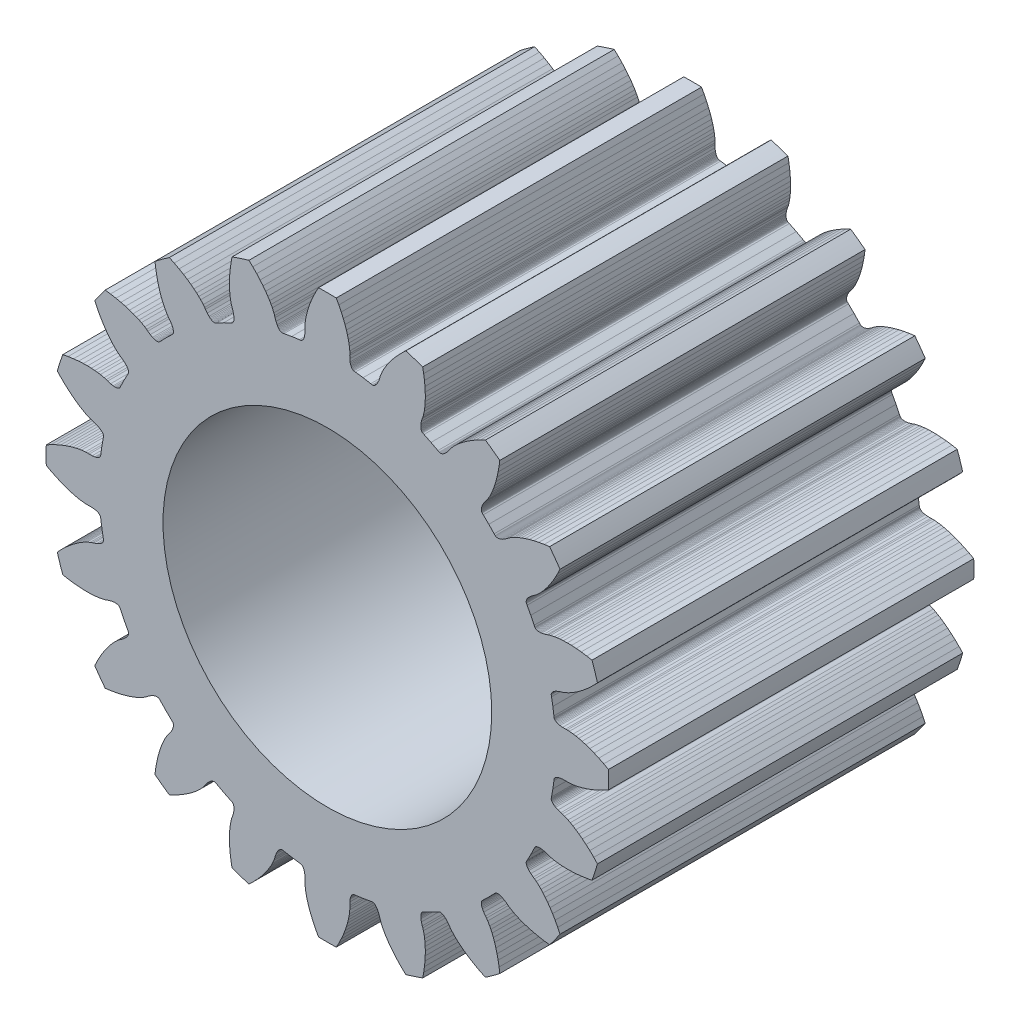
SolidWorks part; units mm, degrees
ref_plane "Front Plane" through (0, 0, 0) normal (0, 0, 1) x (1, 0, 0)
ref_plane "Top Plane" through (0, 0, 0) normal (0, 1, 0) x (1, 0, 0)
ref_plane "Right Plane" through (0, 0, 0) normal (1, 0, 0) x (0, 0, -1)
sketch "Model" plane through (0, 0, 0) normal (0, 0, 1) x (1, 0, 0)
  line L0 (7.2933, 2.0404) -> (7.1846, 1.9349)
  line L1 (7.1846, 1.9349) -> (7.0807, 1.8421)
  line L2 (7.0807, 1.8421) -> (6.9818, 1.761)
  line L3 (6.9818, 1.761) -> (6.8887, 1.6909)
  line L4 (6.8887, 1.6909) -> (6.8014, 1.6307)
  line L5 (6.8014, 1.6307) -> (6.7217, 1.5806)
  line L6 (6.7217, 1.5806) -> (6.6519, 1.5406)
  line L7 (6.6519, 1.5406) -> (6.5879, 1.5074)
  line L8 (6.5879, 1.5074) -> (6.4907, 1.4643)
  line L9 (6.4907, 1.4643) -> (6.4338, 1.4443)
  line L10 (6.4338, 1.4443) -> (6.3923, 1.4329)
  line L11 (6.3923, 1.4329) -> (6.3144, 1.4064)
  line L12 (6.3144, 1.4064) -> (6.25, 1.3764)
  line L13 (6.25, 1.3764) -> (6.2229, 1.3604)
  line L14 (6.2229, 1.3604) -> (6.1992, 1.3439)
  line L15 (6.1992, 1.3439) -> (6.1789, 1.3271)
  line L16 (6.1789, 1.3271) -> (6.162, 1.3101)
  line L17 (6.162, 1.3101) -> (6.1485, 1.2931)
  line L18 (6.1485, 1.2931) -> (6.1385, 1.2761)
  line L19 (6.1385, 1.2761) -> (6.1318, 1.2594)
  line L20 (6.1318, 1.2594) -> (6.1285, 1.2429)
  line L21 (6.1285, 1.2429) -> (6.1286, 1.227)
  line L22 (6.1286, 1.227) -> (6.1363, 1.1869)
  line L23 (6.1363, 1.1869) -> (6.1731, 0.9777)
  line L24 (6.1731, 0.9777) -> (6.2027, 0.7674)
  line L25 (6.2027, 0.7674) -> (6.2078, 0.7269)
  line L26 (6.2078, 0.7269) -> (6.2127, 0.7117)
  line L27 (6.2127, 0.7117) -> (6.2209, 0.6971)
  line L28 (6.2209, 0.6971) -> (6.2324, 0.6832)
  line L29 (6.2324, 0.6832) -> (6.2472, 0.6702)
  line L30 (6.2472, 0.6702) -> (6.2653, 0.6581)
  line L31 (6.2653, 0.6581) -> (6.2866, 0.6472)
  line L32 (6.2866, 0.6472) -> (6.311, 0.6375)
  line L33 (6.311, 0.6375) -> (6.3387, 0.6292)
  line L34 (6.3387, 0.6292) -> (6.3694, 0.6224)
  line L35 (6.3694, 0.6224) -> (6.44, 0.6137)
  line L36 (6.44, 0.6137) -> (6.5223, 0.6125)
  line L37 (6.5223, 0.6125) -> (6.5653, 0.6145)
  line L38 (6.5653, 0.6145) -> (6.6255, 0.6131)
  line L39 (6.6255, 0.6131) -> (6.7313, 0.6021)
  line L40 (6.7313, 0.6021) -> (6.8024, 0.5904)
  line L41 (6.8024, 0.5904) -> (6.8812, 0.5739)
  line L42 (6.8812, 0.5739) -> (6.9724, 0.5509)
  line L43 (6.9724, 0.5509) -> (7.0741, 0.5206)
  line L44 (7.0741, 0.5206) -> (7.1843, 0.4827)
  line L45 (7.1843, 0.4827) -> (7.3033, 0.4361)
  line L46 (7.3033, 0.4361) -> (7.4309, 0.38)
  line L47 (7.4309, 0.38) -> (7.5669, 0.3132)
  line L48 (7.5669, 0.3132) -> (7.6962, 0.2431)
  line L49 (7.6962, -0.2431) -> (7.5669, -0.3132)
  line L50 (7.5669, -0.3132) -> (7.4309, -0.38)
  line L51 (7.4309, -0.38) -> (7.3033, -0.4361)
  line L52 (7.3033, -0.4361) -> (7.1843, -0.4827)
  line L53 (7.1843, -0.4827) -> (7.0741, -0.5206)
  line L54 (7.0741, -0.5206) -> (6.9724, -0.5509)
  line L55 (6.9724, -0.5509) -> (6.8812, -0.5739)
  line L56 (6.8812, -0.5739) -> (6.8024, -0.5904)
  line L57 (6.8024, -0.5904) -> (6.7313, -0.6021)
  line L58 (6.7313, -0.6021) -> (6.6255, -0.6131)
  line L59 (6.6255, -0.6131) -> (6.5653, -0.6145)
  line L60 (6.5653, -0.6145) -> (6.5223, -0.6125)
  line L61 (6.5223, -0.6125) -> (6.44, -0.6137)
  line L62 (6.44, -0.6137) -> (6.3694, -0.6224)
  line L63 (6.3694, -0.6224) -> (6.3387, -0.6292)
  line L64 (6.3387, -0.6292) -> (6.311, -0.6375)
  line L65 (6.311, -0.6375) -> (6.2866, -0.6472)
  line L66 (6.2866, -0.6472) -> (6.2653, -0.6581)
  line L67 (6.2653, -0.6581) -> (6.2472, -0.6702)
  line L68 (6.2472, -0.6702) -> (6.2324, -0.6832)
  line L69 (6.2324, -0.6832) -> (6.2209, -0.6971)
  line L70 (6.2209, -0.6971) -> (6.2127, -0.7117)
  line L71 (6.2127, -0.7117) -> (6.2078, -0.7269)
  line L72 (6.2078, -0.7269) -> (6.2027, -0.7674)
  line L73 (6.2027, -0.7674) -> (6.1731, -0.9777)
  line L74 (6.1731, -0.9777) -> (6.1363, -1.1869)
  line L75 (6.1363, -1.1869) -> (6.1286, -1.227)
  line L76 (6.1286, -1.227) -> (6.1285, -1.2429)
  line L77 (6.1285, -1.2429) -> (6.1318, -1.2594)
  line L78 (6.1318, -1.2594) -> (6.1385, -1.2761)
  line L79 (6.1385, -1.2761) -> (6.1485, -1.2931)
  line L80 (6.1485, -1.2931) -> (6.162, -1.3101)
  line L81 (6.162, -1.3101) -> (6.1789, -1.3271)
  line L82 (6.1789, -1.3271) -> (6.1992, -1.3439)
  line L83 (6.1992, -1.3439) -> (6.2229, -1.3604)
  line L84 (6.2229, -1.3604) -> (6.25, -1.3764)
  line L85 (6.25, -1.3764) -> (6.3144, -1.4064)
  line L86 (6.3144, -1.4064) -> (6.3923, -1.4329)
  line L87 (6.3923, -1.4329) -> (6.4338, -1.4443)
  line L88 (6.4338, -1.4443) -> (6.4907, -1.4643)
  line L89 (6.4907, -1.4643) -> (6.5879, -1.5074)
  line L90 (6.5879, -1.5074) -> (6.6519, -1.5406)
  line L91 (6.6519, -1.5406) -> (6.7217, -1.5806)
  line L92 (6.7217, -1.5806) -> (6.8014, -1.6307)
  line L93 (6.8014, -1.6307) -> (6.8887, -1.6909)
  line L94 (6.8887, -1.6909) -> (6.9818, -1.761)
  line L95 (6.9818, -1.761) -> (7.0807, -1.8421)
  line L96 (7.0807, -1.8421) -> (7.1846, -1.9349)
  line L97 (7.1846, -1.9349) -> (7.2933, -2.0404)
  line L98 (7.2933, -2.0404) -> (7.3946, -2.1471)
  line L99 (7.2444, -2.6094) -> (7.0997, -2.6362)
  line L100 (7.0997, -2.6362) -> (6.9497, -2.6577)
  line L101 (6.9497, -2.6577) -> (6.8111, -2.6716)
  line L102 (6.8111, -2.6716) -> (6.6835, -2.6791)
  line L103 (6.6835, -2.6791) -> (6.5669, -2.6811)
  line L104 (6.5669, -2.6811) -> (6.4609, -2.6785)
  line L105 (6.4609, -2.6785) -> (6.367, -2.6722)
  line L106 (6.367, -2.6722) -> (6.2871, -2.6635)
  line L107 (6.2871, -2.6635) -> (6.2158, -2.6528)
  line L108 (6.2158, -2.6528) -> (6.1118, -2.6305)
  line L109 (6.1118, -2.6305) -> (6.054, -2.6132)
  line L110 (6.054, -2.6132) -> (6.0137, -2.5981)
  line L111 (6.0137, -2.5981) -> (5.9351, -2.5737)
  line L112 (5.9351, -2.5737) -> (5.8654, -2.5602)
  line L113 (5.8654, -2.5602) -> (5.834, -2.5572)
  line L114 (5.834, -2.5572) -> (5.8052, -2.5565)
  line L115 (5.8052, -2.5565) -> (5.7789, -2.5582)
  line L116 (5.7789, -2.5582) -> (5.7552, -2.562)
  line L117 (5.7552, -2.562) -> (5.7343, -2.5679)
  line L118 (5.7343, -2.5679) -> (5.7162, -2.5757)
  line L119 (5.7162, -2.5757) -> (5.701, -2.5853)
  line L120 (5.701, -2.5853) -> (5.6887, -2.5967)
  line L121 (5.6887, -2.5967) -> (5.6794, -2.6096)
  line L122 (5.6794, -2.6096) -> (5.662, -2.6466)
  line L123 (5.662, -2.6466) -> (5.5688, -2.8374)
  line L124 (5.5688, -2.8374) -> (5.4692, -3.025)
  line L125 (5.4692, -3.025) -> (5.4495, -3.0608)
  line L126 (5.4495, -3.0608) -> (5.4445, -3.0759)
  line L127 (5.4445, -3.0759) -> (5.4425, -3.0926)
  line L128 (5.4425, -3.0926) -> (5.4437, -3.1106)
  line L129 (5.4437, -3.1106) -> (5.448, -3.1298)
  line L130 (5.448, -3.1298) -> (5.4555, -3.1502)
  line L131 (5.4555, -3.1502) -> (5.4663, -3.1715)
  line L132 (5.4663, -3.1715) -> (5.4805, -3.1938)
  line L133 (5.4805, -3.1938) -> (5.4979, -3.2168)
  line L134 (5.4979, -3.2168) -> (5.5188, -3.2404)
  line L135 (5.5188, -3.2404) -> (5.5708, -3.2888)
  line L136 (5.5708, -3.2888) -> (5.6367, -3.3381)
  line L137 (5.6367, -3.3381) -> (5.6726, -3.3618)
  line L138 (5.6726, -3.3618) -> (5.7205, -3.3983)
  line L139 (5.7205, -3.3983) -> (5.7997, -3.4694)
  line L140 (5.7997, -3.4694) -> (5.8503, -3.5208)
  line L141 (5.8503, -3.5208) -> (5.9043, -3.5803)
  line L142 (5.9043, -3.5803) -> (5.9646, -3.6526)
  line L143 (5.9646, -3.6526) -> (6.029, -3.7368)
  line L144 (6.029, -3.7368) -> (6.096, -3.8323)
  line L145 (6.096, -3.8323) -> (6.1649, -3.94)
  line L146 (6.1649, -3.94) -> (6.235, -4.0603)
  line L147 (6.235, -4.0603) -> (6.3058, -4.1943)
  line L148 (6.3058, -4.1943) -> (6.3692, -4.327)
  line L149 (6.0834, -4.7203) -> (5.9376, -4.7011)
  line L150 (5.9376, -4.7011) -> (5.7883, -4.6752)
  line L151 (5.7883, -4.6752) -> (5.6522, -4.6456)
  line L152 (5.6522, -4.6456) -> (5.5285, -4.6133)
  line L153 (5.5285, -4.6133) -> (5.417, -4.5792)
  line L154 (5.417, -4.5792) -> (5.317, -4.544)
  line L155 (5.317, -4.544) -> (5.2296, -4.509)
  line L156 (5.2296, -4.509) -> (5.1563, -4.476)
  line L157 (5.1563, -4.476) -> (5.0918, -4.4437)
  line L158 (5.0918, -4.4437) -> (4.9997, -4.3904)
  line L159 (4.9997, -4.3904) -> (4.9502, -4.3561)
  line L160 (4.9502, -4.3561) -> (4.9166, -4.3292)
  line L161 (4.9166, -4.3292) -> (4.8493, -4.2818)
  line L162 (4.8493, -4.2818) -> (4.7872, -4.2474)
  line L163 (4.7872, -4.2474) -> (4.7583, -4.2348)
  line L164 (4.7583, -4.2348) -> (4.731, -4.2253)
  line L165 (4.731, -4.2253) -> (4.7055, -4.2187)
  line L166 (4.7055, -4.2187) -> (4.6819, -4.2151)
  line L167 (4.6819, -4.2151) -> (4.6601, -4.2142)
  line L168 (4.6601, -4.2142) -> (4.6405, -4.216)
  line L169 (4.6405, -4.216) -> (4.623, -4.2205)
  line L170 (4.623, -4.2205) -> (4.6078, -4.2275)
  line L171 (4.6078, -4.2275) -> (4.595, -4.2369)
  line L172 (4.595, -4.2369) -> (4.567, -4.2667)
  line L173 (4.567, -4.2667) -> (4.4194, -4.4194)
  line L174 (4.4194, -4.4194) -> (4.2667, -4.567)
  line L175 (4.2667, -4.567) -> (4.2369, -4.595)
  line L176 (4.2369, -4.595) -> (4.2275, -4.6078)
  line L177 (4.2275, -4.6078) -> (4.2205, -4.623)
  line L178 (4.2205, -4.623) -> (4.216, -4.6405)
  line L179 (4.216, -4.6405) -> (4.2142, -4.6601)
  line L180 (4.2142, -4.6601) -> (4.2151, -4.6819)
  line L181 (4.2151, -4.6819) -> (4.2187, -4.7055)
  line L182 (4.2187, -4.7055) -> (4.2253, -4.731)
  line L183 (4.2253, -4.731) -> (4.2348, -4.7583)
  line L184 (4.2348, -4.7583) -> (4.2474, -4.7872)
  line L185 (4.2474, -4.7872) -> (4.2818, -4.8493)
  line L186 (4.2818, -4.8493) -> (4.3292, -4.9166)
  line L187 (4.3292, -4.9166) -> (4.3561, -4.9502)
  line L188 (4.3561, -4.9502) -> (4.3904, -4.9997)
  line L189 (4.3904, -4.9997) -> (4.4437, -5.0918)
  line L190 (4.4437, -5.0918) -> (4.476, -5.1563)
  line L191 (4.476, -5.1563) -> (4.509, -5.2296)
  line L192 (4.509, -5.2296) -> (4.544, -5.317)
  line L193 (4.544, -5.317) -> (4.5792, -5.417)
  line L194 (4.5792, -5.417) -> (4.6133, -5.5285)
  line L195 (4.6133, -5.5285) -> (4.6456, -5.6522)
  line L196 (4.6456, -5.6522) -> (4.6752, -5.7883)
  line L197 (4.6752, -5.7883) -> (4.7011, -5.9376)
  line L198 (4.7011, -5.9376) -> (4.7203, -6.0834)
  line L199 (4.327, -6.3692) -> (4.1943, -6.3058)
  line L200 (4.1943, -6.3058) -> (4.0603, -6.235)
  line L201 (4.0603, -6.235) -> (3.94, -6.1649)
  line L202 (3.94, -6.1649) -> (3.8323, -6.096)
  line L203 (3.8323, -6.096) -> (3.7368, -6.029)
  line L204 (3.7368, -6.029) -> (3.6526, -5.9646)
  line L205 (3.6526, -5.9646) -> (3.5803, -5.9043)
  line L206 (3.5803, -5.9043) -> (3.5208, -5.8503)
  line L207 (3.5208, -5.8503) -> (3.4694, -5.7997)
  line L208 (3.4694, -5.7997) -> (3.3983, -5.7205)
  line L209 (3.3983, -5.7205) -> (3.3618, -5.6726)
  line L210 (3.3618, -5.6726) -> (3.3381, -5.6367)
  line L211 (3.3381, -5.6367) -> (3.2888, -5.5708)
  line L212 (3.2888, -5.5708) -> (3.2404, -5.5188)
  line L213 (3.2404, -5.5188) -> (3.2168, -5.4979)
  line L214 (3.2168, -5.4979) -> (3.1938, -5.4805)
  line L215 (3.1938, -5.4805) -> (3.1715, -5.4663)
  line L216 (3.1715, -5.4663) -> (3.1502, -5.4555)
  line L217 (3.1502, -5.4555) -> (3.1298, -5.448)
  line L218 (3.1298, -5.448) -> (3.1106, -5.4437)
  line L219 (3.1106, -5.4437) -> (3.0926, -5.4425)
  line L220 (3.0926, -5.4425) -> (3.0759, -5.4445)
  line L221 (3.0759, -5.4445) -> (3.0608, -5.4495)
  line L222 (3.0608, -5.4495) -> (3.025, -5.4692)
  line L223 (3.025, -5.4692) -> (2.8374, -5.5688)
  line L224 (2.8374, -5.5688) -> (2.6466, -5.662)
  line L225 (2.6466, -5.662) -> (2.6096, -5.6794)
  line L226 (2.6096, -5.6794) -> (2.5967, -5.6887)
  line L227 (2.5967, -5.6887) -> (2.5853, -5.701)
  line L228 (2.5853, -5.701) -> (2.5757, -5.7162)
  line L229 (2.5757, -5.7162) -> (2.5679, -5.7343)
  line L230 (2.5679, -5.7343) -> (2.562, -5.7552)
  line L231 (2.562, -5.7552) -> (2.5582, -5.7789)
  line L232 (2.5582, -5.7789) -> (2.5565, -5.8052)
  line L233 (2.5565, -5.8052) -> (2.5572, -5.834)
  line L234 (2.5572, -5.834) -> (2.5602, -5.8654)
  line L235 (2.5602, -5.8654) -> (2.5737, -5.9351)
  line L236 (2.5737, -5.9351) -> (2.5981, -6.0137)
  line L237 (2.5981, -6.0137) -> (2.6132, -6.054)
  line L238 (2.6132, -6.054) -> (2.6305, -6.1118)
  line L239 (2.6305, -6.1118) -> (2.6528, -6.2158)
  line L240 (2.6528, -6.2158) -> (2.6635, -6.2871)
  line L241 (2.6635, -6.2871) -> (2.6722, -6.367)
  line L242 (2.6722, -6.367) -> (2.6785, -6.4609)
  line L243 (2.6785, -6.4609) -> (2.6811, -6.5669)
  line L244 (2.6811, -6.5669) -> (2.6791, -6.6835)
  line L245 (2.6791, -6.6835) -> (2.6716, -6.8111)
  line L246 (2.6716, -6.8111) -> (2.6577, -6.9497)
  line L247 (2.6577, -6.9497) -> (2.6362, -7.0997)
  line L248 (2.6362, -7.0997) -> (2.6094, -7.2444)
  line L249 (2.1471, -7.3946) -> (2.0404, -7.2933)
  line L250 (2.0404, -7.2933) -> (1.9349, -7.1846)
  line L251 (1.9349, -7.1846) -> (1.8421, -7.0807)
  line L252 (1.8421, -7.0807) -> (1.761, -6.9818)
  line L253 (1.761, -6.9818) -> (1.6909, -6.8887)
  line L254 (1.6909, -6.8887) -> (1.6307, -6.8014)
  line L255 (1.6307, -6.8014) -> (1.5806, -6.7217)
  line L256 (1.5806, -6.7217) -> (1.5406, -6.6519)
  line L257 (1.5406, -6.6519) -> (1.5074, -6.5879)
  line L258 (1.5074, -6.5879) -> (1.4643, -6.4907)
  line L259 (1.4643, -6.4907) -> (1.4443, -6.4338)
  line L260 (1.4443, -6.4338) -> (1.4329, -6.3923)
  line L261 (1.4329, -6.3923) -> (1.4064, -6.3144)
  line L262 (1.4064, -6.3144) -> (1.3764, -6.25)
  line L263 (1.3764, -6.25) -> (1.3604, -6.2229)
  line L264 (1.3604, -6.2229) -> (1.3439, -6.1992)
  line L265 (1.3439, -6.1992) -> (1.3271, -6.1789)
  line L266 (1.3271, -6.1789) -> (1.3101, -6.162)
  line L267 (1.3101, -6.162) -> (1.2931, -6.1485)
  line L268 (1.2931, -6.1485) -> (1.2761, -6.1385)
  line L269 (1.2761, -6.1385) -> (1.2594, -6.1318)
  line L270 (1.2594, -6.1318) -> (1.2429, -6.1285)
  line L271 (1.2429, -6.1285) -> (1.227, -6.1286)
  line L272 (1.227, -6.1286) -> (1.1869, -6.1363)
  line L273 (1.1869, -6.1363) -> (0.9777, -6.1731)
  line L274 (0.9777, -6.1731) -> (0.7674, -6.2027)
  line L275 (0.7674, -6.2027) -> (0.7269, -6.2078)
  line L276 (0.7269, -6.2078) -> (0.7117, -6.2127)
  line L277 (0.7117, -6.2127) -> (0.6971, -6.2209)
  line L278 (0.6971, -6.2209) -> (0.6832, -6.2324)
  line L279 (0.6832, -6.2324) -> (0.6702, -6.2472)
  line L280 (0.6702, -6.2472) -> (0.6581, -6.2653)
  line L281 (0.6581, -6.2653) -> (0.6472, -6.2866)
  line L282 (0.6472, -6.2866) -> (0.6375, -6.311)
  line L283 (0.6375, -6.311) -> (0.6292, -6.3387)
  line L284 (0.6292, -6.3387) -> (0.6224, -6.3694)
  line L285 (0.6224, -6.3694) -> (0.6137, -6.44)
  line L286 (0.6137, -6.44) -> (0.6125, -6.5223)
  line L287 (0.6125, -6.5223) -> (0.6145, -6.5653)
  line L288 (0.6145, -6.5653) -> (0.6131, -6.6255)
  line L289 (0.6131, -6.6255) -> (0.6021, -6.7313)
  line L290 (0.6021, -6.7313) -> (0.5904, -6.8024)
  line L291 (0.5904, -6.8024) -> (0.5739, -6.8812)
  line L292 (0.5739, -6.8812) -> (0.5509, -6.9724)
  line L293 (0.5509, -6.9724) -> (0.5206, -7.0741)
  line L294 (0.5206, -7.0741) -> (0.4827, -7.1843)
  line L295 (0.4827, -7.1843) -> (0.4361, -7.3033)
  line L296 (0.4361, -7.3033) -> (0.38, -7.4309)
  line L297 (0.38, -7.4309) -> (0.3132, -7.5669)
  line L298 (0.3132, -7.5669) -> (0.2431, -7.6962)
  line L299 (-0.2431, -7.6962) -> (-0.3132, -7.5669)
  line L300 (-0.3132, -7.5669) -> (-0.38, -7.4309)
  line L301 (-0.38, -7.4309) -> (-0.4361, -7.3033)
  line L302 (-0.4361, -7.3033) -> (-0.4827, -7.1843)
  line L303 (-0.4827, -7.1843) -> (-0.5206, -7.0741)
  line L304 (-0.5206, -7.0741) -> (-0.5509, -6.9724)
  line L305 (-0.5509, -6.9724) -> (-0.5739, -6.8812)
  line L306 (-0.5739, -6.8812) -> (-0.5904, -6.8024)
  line L307 (-0.5904, -6.8024) -> (-0.6021, -6.7313)
  line L308 (-0.6021, -6.7313) -> (-0.6131, -6.6255)
  line L309 (-0.6131, -6.6255) -> (-0.6145, -6.5653)
  line L310 (-0.6145, -6.5653) -> (-0.6125, -6.5223)
  line L311 (-0.6125, -6.5223) -> (-0.6137, -6.44)
  line L312 (-0.6137, -6.44) -> (-0.6224, -6.3694)
  line L313 (-0.6224, -6.3694) -> (-0.6292, -6.3387)
  line L314 (-0.6292, -6.3387) -> (-0.6375, -6.311)
  line L315 (-0.6375, -6.311) -> (-0.6472, -6.2866)
  line L316 (-0.6472, -6.2866) -> (-0.6581, -6.2653)
  line L317 (-0.6581, -6.2653) -> (-0.6702, -6.2472)
  line L318 (-0.6702, -6.2472) -> (-0.6832, -6.2324)
  line L319 (-0.6832, -6.2324) -> (-0.6971, -6.2209)
  line L320 (-0.6971, -6.2209) -> (-0.7117, -6.2127)
  line L321 (-0.7117, -6.2127) -> (-0.7269, -6.2078)
  line L322 (-0.7269, -6.2078) -> (-0.7674, -6.2027)
  line L323 (-0.7674, -6.2027) -> (-0.9777, -6.1731)
  line L324 (-0.9777, -6.1731) -> (-1.1869, -6.1363)
  line L325 (-1.1869, -6.1363) -> (-1.227, -6.1286)
  line L326 (-1.227, -6.1286) -> (-1.2429, -6.1285)
  line L327 (-1.2429, -6.1285) -> (-1.2594, -6.1318)
  line L328 (-1.2594, -6.1318) -> (-1.2761, -6.1385)
  line L329 (-1.2761, -6.1385) -> (-1.2931, -6.1485)
  line L330 (-1.2931, -6.1485) -> (-1.3101, -6.162)
  line L331 (-1.3101, -6.162) -> (-1.3271, -6.1789)
  line L332 (-1.3271, -6.1789) -> (-1.3439, -6.1992)
  line L333 (-1.3439, -6.1992) -> (-1.3604, -6.2229)
  line L334 (-1.3604, -6.2229) -> (-1.3764, -6.25)
  line L335 (-1.3764, -6.25) -> (-1.4064, -6.3144)
  line L336 (-1.4064, -6.3144) -> (-1.4329, -6.3923)
  line L337 (-1.4329, -6.3923) -> (-1.4443, -6.4338)
  line L338 (-1.4443, -6.4338) -> (-1.4643, -6.4907)
  line L339 (-1.4643, -6.4907) -> (-1.5074, -6.5879)
  line L340 (-1.5074, -6.5879) -> (-1.5406, -6.6519)
  line L341 (-1.5406, -6.6519) -> (-1.5806, -6.7217)
  line L342 (-1.5806, -6.7217) -> (-1.6307, -6.8014)
  line L343 (-1.6307, -6.8014) -> (-1.6909, -6.8887)
  line L344 (-1.6909, -6.8887) -> (-1.761, -6.9818)
  line L345 (-1.761, -6.9818) -> (-1.8421, -7.0807)
  line L346 (-1.8421, -7.0807) -> (-1.9349, -7.1846)
  line L347 (-1.9349, -7.1846) -> (-2.0404, -7.2933)
  line L348 (-2.0404, -7.2933) -> (-2.1471, -7.3946)
  line L349 (-2.6094, -7.2444) -> (-2.6362, -7.0997)
  line L350 (-2.6362, -7.0997) -> (-2.6577, -6.9497)
  line L351 (-2.6577, -6.9497) -> (-2.6716, -6.8111)
  line L352 (-2.6716, -6.8111) -> (-2.6791, -6.6835)
  line L353 (-2.6791, -6.6835) -> (-2.6811, -6.5669)
  line L354 (-2.6811, -6.5669) -> (-2.6785, -6.4609)
  line L355 (-2.6785, -6.4609) -> (-2.6722, -6.367)
  line L356 (-2.6722, -6.367) -> (-2.6635, -6.2871)
  line L357 (-2.6635, -6.2871) -> (-2.6528, -6.2158)
  line L358 (-2.6528, -6.2158) -> (-2.6305, -6.1118)
  line L359 (-2.6305, -6.1118) -> (-2.6132, -6.054)
  line L360 (-2.6132, -6.054) -> (-2.5981, -6.0137)
  line L361 (-2.5981, -6.0137) -> (-2.5737, -5.9351)
  line L362 (-2.5737, -5.9351) -> (-2.5602, -5.8654)
  line L363 (-2.5602, -5.8654) -> (-2.5572, -5.834)
  line L364 (-2.5572, -5.834) -> (-2.5565, -5.8052)
  line L365 (-2.5565, -5.8052) -> (-2.5582, -5.7789)
  line L366 (-2.5582, -5.7789) -> (-2.562, -5.7552)
  line L367 (-2.562, -5.7552) -> (-2.5679, -5.7343)
  line L368 (-2.5679, -5.7343) -> (-2.5757, -5.7162)
  line L369 (-2.5757, -5.7162) -> (-2.5853, -5.701)
  line L370 (-2.5853, -5.701) -> (-2.5967, -5.6887)
  line L371 (-2.5967, -5.6887) -> (-2.6096, -5.6794)
  line L372 (-2.6096, -5.6794) -> (-2.6466, -5.662)
  line L373 (-2.6466, -5.662) -> (-2.8374, -5.5688)
  line L374 (-2.8374, -5.5688) -> (-3.025, -5.4692)
  line L375 (-3.025, -5.4692) -> (-3.0608, -5.4495)
  line L376 (-3.0608, -5.4495) -> (-3.0759, -5.4445)
  line L377 (-3.0759, -5.4445) -> (-3.0926, -5.4425)
  line L378 (-3.0926, -5.4425) -> (-3.1106, -5.4437)
  line L379 (-3.1106, -5.4437) -> (-3.1298, -5.448)
  line L380 (-3.1298, -5.448) -> (-3.1502, -5.4555)
  line L381 (-3.1502, -5.4555) -> (-3.1715, -5.4663)
  line L382 (-3.1715, -5.4663) -> (-3.1938, -5.4805)
  line L383 (-3.1938, -5.4805) -> (-3.2168, -5.4979)
  line L384 (-3.2168, -5.4979) -> (-3.2404, -5.5188)
  line L385 (-3.2404, -5.5188) -> (-3.2888, -5.5708)
  line L386 (-3.2888, -5.5708) -> (-3.3381, -5.6367)
  line L387 (-3.3381, -5.6367) -> (-3.3618, -5.6726)
  line L388 (-3.3618, -5.6726) -> (-3.3983, -5.7205)
  line L389 (-3.3983, -5.7205) -> (-3.4694, -5.7997)
  line L390 (-3.4694, -5.7997) -> (-3.5208, -5.8503)
  line L391 (-3.5208, -5.8503) -> (-3.5803, -5.9043)
  line L392 (-3.5803, -5.9043) -> (-3.6526, -5.9646)
  line L393 (-3.6526, -5.9646) -> (-3.7368, -6.029)
  line L394 (-3.7368, -6.029) -> (-3.8323, -6.096)
  line L395 (-3.8323, -6.096) -> (-3.94, -6.1649)
  line L396 (-3.94, -6.1649) -> (-4.0603, -6.235)
  line L397 (-4.0603, -6.235) -> (-4.1943, -6.3058)
  line L398 (-4.1943, -6.3058) -> (-4.327, -6.3692)
  line L399 (-4.7203, -6.0834) -> (-4.7011, -5.9376)
  line L400 (-4.7011, -5.9376) -> (-4.6752, -5.7883)
  line L401 (-4.6752, -5.7883) -> (-4.6456, -5.6522)
  line L402 (-4.6456, -5.6522) -> (-4.6133, -5.5285)
  line L403 (-4.6133, -5.5285) -> (-4.5792, -5.417)
  line L404 (-4.5792, -5.417) -> (-4.544, -5.317)
  line L405 (-4.544, -5.317) -> (-4.509, -5.2296)
  line L406 (-4.509, -5.2296) -> (-4.476, -5.1563)
  line L407 (-4.476, -5.1563) -> (-4.4437, -5.0918)
  line L408 (-4.4437, -5.0918) -> (-4.3904, -4.9997)
  line L409 (-4.3904, -4.9997) -> (-4.3561, -4.9502)
  line L410 (-4.3561, -4.9502) -> (-4.3292, -4.9166)
  line L411 (-4.3292, -4.9166) -> (-4.2818, -4.8493)
  line L412 (-4.2818, -4.8493) -> (-4.2474, -4.7872)
  line L413 (-4.2474, -4.7872) -> (-4.2348, -4.7583)
  line L414 (-4.2348, -4.7583) -> (-4.2253, -4.731)
  line L415 (-4.2253, -4.731) -> (-4.2187, -4.7055)
  line L416 (-4.2187, -4.7055) -> (-4.2151, -4.6819)
  line L417 (-4.2151, -4.6819) -> (-4.2142, -4.6601)
  line L418 (-4.2142, -4.6601) -> (-4.216, -4.6405)
  line L419 (-4.216, -4.6405) -> (-4.2205, -4.623)
  line L420 (-4.2205, -4.623) -> (-4.2275, -4.6078)
  line L421 (-4.2275, -4.6078) -> (-4.2369, -4.595)
  line L422 (-4.2369, -4.595) -> (-4.2667, -4.567)
  line L423 (-4.2667, -4.567) -> (-4.4194, -4.4194)
  line L424 (-4.4194, -4.4194) -> (-4.567, -4.2667)
  line L425 (-4.567, -4.2667) -> (-4.595, -4.2369)
  line L426 (-4.595, -4.2369) -> (-4.6078, -4.2275)
  line L427 (-4.6078, -4.2275) -> (-4.623, -4.2205)
  line L428 (-4.623, -4.2205) -> (-4.6405, -4.216)
  line L429 (-4.6405, -4.216) -> (-4.6601, -4.2142)
  line L430 (-4.6601, -4.2142) -> (-4.6819, -4.2151)
  line L431 (-4.6819, -4.2151) -> (-4.7055, -4.2187)
  line L432 (-4.7055, -4.2187) -> (-4.731, -4.2253)
  line L433 (-4.731, -4.2253) -> (-4.7583, -4.2348)
  line L434 (-4.7583, -4.2348) -> (-4.7872, -4.2474)
  line L435 (-4.7872, -4.2474) -> (-4.8493, -4.2818)
  line L436 (-4.8493, -4.2818) -> (-4.9166, -4.3292)
  line L437 (-4.9166, -4.3292) -> (-4.9502, -4.3561)
  line L438 (-4.9502, -4.3561) -> (-4.9997, -4.3904)
  line L439 (-4.9997, -4.3904) -> (-5.0918, -4.4437)
  line L440 (-5.0918, -4.4437) -> (-5.1563, -4.476)
  line L441 (-5.1563, -4.476) -> (-5.2296, -4.509)
  line L442 (-5.2296, -4.509) -> (-5.317, -4.544)
  line L443 (-5.317, -4.544) -> (-5.417, -4.5792)
  line L444 (-5.417, -4.5792) -> (-5.5285, -4.6133)
  line L445 (-5.5285, -4.6133) -> (-5.6522, -4.6456)
  line L446 (-5.6522, -4.6456) -> (-5.7883, -4.6752)
  line L447 (-5.7883, -4.6752) -> (-5.9376, -4.7011)
  line L448 (-5.9376, -4.7011) -> (-6.0834, -4.7203)
  line L449 (-6.3692, -4.327) -> (-6.3058, -4.1943)
  line L450 (-6.3058, -4.1943) -> (-6.235, -4.0603)
  line L451 (-6.235, -4.0603) -> (-6.1649, -3.94)
  line L452 (-6.1649, -3.94) -> (-6.096, -3.8323)
  line L453 (-6.096, -3.8323) -> (-6.029, -3.7368)
  line L454 (-6.029, -3.7368) -> (-5.9646, -3.6526)
  line L455 (-5.9646, -3.6526) -> (-5.9043, -3.5803)
  line L456 (-5.9043, -3.5803) -> (-5.8503, -3.5208)
  line L457 (-5.8503, -3.5208) -> (-5.7997, -3.4694)
  line L458 (-5.7997, -3.4694) -> (-5.7205, -3.3983)
  line L459 (-5.7205, -3.3983) -> (-5.6726, -3.3618)
  line L460 (-5.6726, -3.3618) -> (-5.6367, -3.3381)
  line L461 (-5.6367, -3.3381) -> (-5.5708, -3.2888)
  line L462 (-5.5708, -3.2888) -> (-5.5188, -3.2404)
  line L463 (-5.5188, -3.2404) -> (-5.4979, -3.2168)
  line L464 (-5.4979, -3.2168) -> (-5.4805, -3.1938)
  line L465 (-5.4805, -3.1938) -> (-5.4663, -3.1715)
  line L466 (-5.4663, -3.1715) -> (-5.4555, -3.1502)
  line L467 (-5.4555, -3.1502) -> (-5.448, -3.1298)
  line L468 (-5.448, -3.1298) -> (-5.4437, -3.1106)
  line L469 (-5.4437, -3.1106) -> (-5.4425, -3.0926)
  line L470 (-5.4425, -3.0926) -> (-5.4445, -3.0759)
  line L471 (-5.4445, -3.0759) -> (-5.4495, -3.0608)
  line L472 (-5.4495, -3.0608) -> (-5.4692, -3.025)
  line L473 (-5.4692, -3.025) -> (-5.5688, -2.8374)
  line L474 (-5.5688, -2.8374) -> (-5.662, -2.6466)
  line L475 (-5.662, -2.6466) -> (-5.6794, -2.6096)
  line L476 (-5.6794, -2.6096) -> (-5.6887, -2.5967)
  line L477 (-5.6887, -2.5967) -> (-5.701, -2.5853)
  line L478 (-5.701, -2.5853) -> (-5.7162, -2.5757)
  line L479 (-5.7162, -2.5757) -> (-5.7343, -2.5679)
  line L480 (-5.7343, -2.5679) -> (-5.7552, -2.562)
  line L481 (-5.7552, -2.562) -> (-5.7789, -2.5582)
  line L482 (-5.7789, -2.5582) -> (-5.8052, -2.5565)
  line L483 (-5.8052, -2.5565) -> (-5.834, -2.5572)
  line L484 (-5.834, -2.5572) -> (-5.8654, -2.5602)
  line L485 (-5.8654, -2.5602) -> (-5.9351, -2.5737)
  line L486 (-5.9351, -2.5737) -> (-6.0137, -2.5981)
  line L487 (-6.0137, -2.5981) -> (-6.054, -2.6132)
  line L488 (-6.054, -2.6132) -> (-6.1118, -2.6305)
  line L489 (-6.1118, -2.6305) -> (-6.2158, -2.6528)
  line L490 (-6.2158, -2.6528) -> (-6.2871, -2.6635)
  line L491 (-6.2871, -2.6635) -> (-6.367, -2.6722)
  line L492 (-6.367, -2.6722) -> (-6.4609, -2.6785)
  line L493 (-6.4609, -2.6785) -> (-6.5669, -2.6811)
  line L494 (-6.5669, -2.6811) -> (-6.6835, -2.6791)
  line L495 (-6.6835, -2.6791) -> (-6.8111, -2.6716)
  line L496 (-6.8111, -2.6716) -> (-6.9497, -2.6577)
  line L497 (-6.9497, -2.6577) -> (-7.0997, -2.6362)
  line L498 (-7.0997, -2.6362) -> (-7.2444, -2.6094)
  line L499 (-7.3946, -2.1471) -> (-7.2933, -2.0404)
  line L500 (-7.2933, -2.0404) -> (-7.1846, -1.9349)
  line L501 (-7.1846, -1.9349) -> (-7.0807, -1.8421)
  line L502 (-7.0807, -1.8421) -> (-6.9818, -1.761)
  line L503 (-6.9818, -1.761) -> (-6.8887, -1.6909)
  line L504 (-6.8887, -1.6909) -> (-6.8014, -1.6307)
  line L505 (-6.8014, -1.6307) -> (-6.7217, -1.5806)
  line L506 (-6.7217, -1.5806) -> (-6.6519, -1.5406)
  line L507 (-6.6519, -1.5406) -> (-6.5879, -1.5074)
  line L508 (-6.5879, -1.5074) -> (-6.4907, -1.4643)
  line L509 (-6.4907, -1.4643) -> (-6.4338, -1.4443)
  line L510 (-6.4338, -1.4443) -> (-6.3923, -1.4329)
  line L511 (-6.3923, -1.4329) -> (-6.3144, -1.4064)
  line L512 (-6.3144, -1.4064) -> (-6.25, -1.3764)
  line L513 (-6.25, -1.3764) -> (-6.2229, -1.3604)
  line L514 (-6.2229, -1.3604) -> (-6.1992, -1.3439)
  line L515 (-6.1992, -1.3439) -> (-6.1789, -1.3271)
  line L516 (-6.1789, -1.3271) -> (-6.162, -1.3101)
  line L517 (-6.162, -1.3101) -> (-6.1485, -1.2931)
  line L518 (-6.1485, -1.2931) -> (-6.1385, -1.2761)
  line L519 (-6.1385, -1.2761) -> (-6.1318, -1.2594)
  line L520 (-6.1318, -1.2594) -> (-6.1285, -1.2429)
  line L521 (-6.1285, -1.2429) -> (-6.1286, -1.227)
  line L522 (-6.1286, -1.227) -> (-6.1363, -1.1869)
  line L523 (-6.1363, -1.1869) -> (-6.1731, -0.9777)
  line L524 (-6.1731, -0.9777) -> (-6.2027, -0.7674)
  line L525 (-6.2027, -0.7674) -> (-6.2078, -0.7269)
  line L526 (-6.2078, -0.7269) -> (-6.2127, -0.7117)
  line L527 (-6.2127, -0.7117) -> (-6.2209, -0.6971)
  line L528 (-6.2209, -0.6971) -> (-6.2324, -0.6832)
  line L529 (-6.2324, -0.6832) -> (-6.2472, -0.6702)
  line L530 (-6.2472, -0.6702) -> (-6.2653, -0.6581)
  line L531 (-6.2653, -0.6581) -> (-6.2866, -0.6472)
  line L532 (-6.2866, -0.6472) -> (-6.311, -0.6375)
  line L533 (-6.311, -0.6375) -> (-6.3387, -0.6292)
  line L534 (-6.3387, -0.6292) -> (-6.3694, -0.6224)
  line L535 (-6.3694, -0.6224) -> (-6.44, -0.6137)
  line L536 (-6.44, -0.6137) -> (-6.5223, -0.6125)
  line L537 (-6.5223, -0.6125) -> (-6.5653, -0.6145)
  line L538 (-6.5653, -0.6145) -> (-6.6255, -0.6131)
  line L539 (-6.6255, -0.6131) -> (-6.7313, -0.6021)
  line L540 (-6.7313, -0.6021) -> (-6.8024, -0.5904)
  line L541 (-6.8024, -0.5904) -> (-6.8812, -0.5739)
  line L542 (-6.8812, -0.5739) -> (-6.9724, -0.5509)
  line L543 (-6.9724, -0.5509) -> (-7.0741, -0.5206)
  line L544 (-7.0741, -0.5206) -> (-7.1843, -0.4827)
  line L545 (-7.1843, -0.4827) -> (-7.3033, -0.4361)
  line L546 (-7.3033, -0.4361) -> (-7.4309, -0.38)
  line L547 (-7.4309, -0.38) -> (-7.5669, -0.3132)
  line L548 (-7.5669, -0.3132) -> (-7.6962, -0.2431)
  line L549 (-7.6962, 0.2431) -> (-7.5669, 0.3132)
  line L550 (-7.5669, 0.3132) -> (-7.4309, 0.38)
  line L551 (-7.4309, 0.38) -> (-7.3033, 0.4361)
  line L552 (-7.3033, 0.4361) -> (-7.1843, 0.4827)
  line L553 (-7.1843, 0.4827) -> (-7.0741, 0.5206)
  line L554 (-7.0741, 0.5206) -> (-6.9724, 0.5509)
  line L555 (-6.9724, 0.5509) -> (-6.8812, 0.5739)
  line L556 (-6.8812, 0.5739) -> (-6.8024, 0.5904)
  line L557 (-6.8024, 0.5904) -> (-6.7313, 0.6021)
  line L558 (-6.7313, 0.6021) -> (-6.6255, 0.6131)
  line L559 (-6.6255, 0.6131) -> (-6.5653, 0.6145)
  line L560 (-6.5653, 0.6145) -> (-6.5223, 0.6125)
  line L561 (-6.5223, 0.6125) -> (-6.44, 0.6137)
  line L562 (-6.44, 0.6137) -> (-6.3694, 0.6224)
  line L563 (-6.3694, 0.6224) -> (-6.3387, 0.6292)
  line L564 (-6.3387, 0.6292) -> (-6.311, 0.6375)
  line L565 (-6.311, 0.6375) -> (-6.2866, 0.6472)
  line L566 (-6.2866, 0.6472) -> (-6.2653, 0.6581)
  line L567 (-6.2653, 0.6581) -> (-6.2472, 0.6702)
  line L568 (-6.2472, 0.6702) -> (-6.2324, 0.6832)
  line L569 (-6.2324, 0.6832) -> (-6.2209, 0.6971)
  line L570 (-6.2209, 0.6971) -> (-6.2127, 0.7117)
  line L571 (-6.2127, 0.7117) -> (-6.2078, 0.7269)
  line L572 (-6.2078, 0.7269) -> (-6.2027, 0.7674)
  line L573 (-6.2027, 0.7674) -> (-6.1731, 0.9777)
  line L574 (-6.1731, 0.9777) -> (-6.1363, 1.1869)
  line L575 (-6.1363, 1.1869) -> (-6.1286, 1.227)
  line L576 (-6.1286, 1.227) -> (-6.1285, 1.2429)
  line L577 (-6.1285, 1.2429) -> (-6.1318, 1.2594)
  line L578 (-6.1318, 1.2594) -> (-6.1385, 1.2761)
  line L579 (-6.1385, 1.2761) -> (-6.1485, 1.2931)
  line L580 (-6.1485, 1.2931) -> (-6.162, 1.3101)
  line L581 (-6.162, 1.3101) -> (-6.1789, 1.3271)
  line L582 (-6.1789, 1.3271) -> (-6.1992, 1.3439)
  line L583 (-6.1992, 1.3439) -> (-6.2229, 1.3604)
  line L584 (-6.2229, 1.3604) -> (-6.25, 1.3764)
  line L585 (-6.25, 1.3764) -> (-6.3144, 1.4064)
  line L586 (-6.3144, 1.4064) -> (-6.3923, 1.4329)
  line L587 (-6.3923, 1.4329) -> (-6.4338, 1.4443)
  line L588 (-6.4338, 1.4443) -> (-6.4907, 1.4643)
  line L589 (-6.4907, 1.4643) -> (-6.5879, 1.5074)
  line L590 (-6.5879, 1.5074) -> (-6.6519, 1.5406)
  line L591 (-6.6519, 1.5406) -> (-6.7217, 1.5806)
  line L592 (-6.7217, 1.5806) -> (-6.8014, 1.6307)
  line L593 (-6.8014, 1.6307) -> (-6.8887, 1.6909)
  line L594 (-6.8887, 1.6909) -> (-6.9818, 1.761)
  line L595 (-6.9818, 1.761) -> (-7.0807, 1.8421)
  line L596 (-7.0807, 1.8421) -> (-7.1846, 1.9349)
  line L597 (-7.1846, 1.9349) -> (-7.2933, 2.0404)
  line L598 (-7.2933, 2.0404) -> (-7.3946, 2.1471)
  line L599 (-7.2444, 2.6094) -> (-7.0997, 2.6362)
  line L600 (-7.0997, 2.6362) -> (-6.9497, 2.6577)
  line L601 (-6.9497, 2.6577) -> (-6.8111, 2.6716)
  line L602 (-6.8111, 2.6716) -> (-6.6835, 2.6791)
  line L603 (-6.6835, 2.6791) -> (-6.5669, 2.6811)
  line L604 (-6.5669, 2.6811) -> (-6.4609, 2.6785)
  line L605 (-6.4609, 2.6785) -> (-6.367, 2.6722)
  line L606 (-6.367, 2.6722) -> (-6.2871, 2.6635)
  line L607 (-6.2871, 2.6635) -> (-6.2158, 2.6528)
  line L608 (-6.2158, 2.6528) -> (-6.1118, 2.6305)
  line L609 (-6.1118, 2.6305) -> (-6.054, 2.6132)
  line L610 (-6.054, 2.6132) -> (-6.0137, 2.5981)
  line L611 (-6.0137, 2.5981) -> (-5.9351, 2.5737)
  line L612 (-5.9351, 2.5737) -> (-5.8654, 2.5602)
  line L613 (-5.8654, 2.5602) -> (-5.834, 2.5572)
  line L614 (-5.834, 2.5572) -> (-5.8052, 2.5565)
  line L615 (-5.8052, 2.5565) -> (-5.7789, 2.5582)
  line L616 (-5.7789, 2.5582) -> (-5.7552, 2.562)
  line L617 (-5.7552, 2.562) -> (-5.7343, 2.5679)
  line L618 (-5.7343, 2.5679) -> (-5.7162, 2.5757)
  line L619 (-5.7162, 2.5757) -> (-5.701, 2.5853)
  line L620 (-5.701, 2.5853) -> (-5.6887, 2.5967)
  line L621 (-5.6887, 2.5967) -> (-5.6794, 2.6096)
  line L622 (-5.6794, 2.6096) -> (-5.662, 2.6466)
  line L623 (-5.662, 2.6466) -> (-5.5688, 2.8374)
  line L624 (-5.5688, 2.8374) -> (-5.4692, 3.025)
  line L625 (-5.4692, 3.025) -> (-5.4495, 3.0608)
  line L626 (-5.4495, 3.0608) -> (-5.4445, 3.0759)
  line L627 (-5.4445, 3.0759) -> (-5.4425, 3.0926)
  line L628 (-5.4425, 3.0926) -> (-5.4437, 3.1106)
  line L629 (-5.4437, 3.1106) -> (-5.448, 3.1298)
  line L630 (-5.448, 3.1298) -> (-5.4555, 3.1502)
  line L631 (-5.4555, 3.1502) -> (-5.4663, 3.1715)
  line L632 (-5.4663, 3.1715) -> (-5.4805, 3.1938)
  line L633 (-5.4805, 3.1938) -> (-5.4979, 3.2168)
  line L634 (-5.4979, 3.2168) -> (-5.5188, 3.2404)
  line L635 (-5.5188, 3.2404) -> (-5.5708, 3.2888)
  line L636 (-5.5708, 3.2888) -> (-5.6367, 3.3381)
  line L637 (-5.6367, 3.3381) -> (-5.6726, 3.3618)
  line L638 (-5.6726, 3.3618) -> (-5.7205, 3.3983)
  line L639 (-5.7205, 3.3983) -> (-5.7997, 3.4694)
  line L640 (-5.7997, 3.4694) -> (-5.8503, 3.5208)
  line L641 (-5.8503, 3.5208) -> (-5.9043, 3.5803)
  line L642 (-5.9043, 3.5803) -> (-5.9646, 3.6526)
  line L643 (-5.9646, 3.6526) -> (-6.029, 3.7368)
  line L644 (-6.029, 3.7368) -> (-6.096, 3.8323)
  line L645 (-6.096, 3.8323) -> (-6.1649, 3.94)
  line L646 (-6.1649, 3.94) -> (-6.235, 4.0603)
  line L647 (-6.235, 4.0603) -> (-6.3058, 4.1943)
  line L648 (-6.3058, 4.1943) -> (-6.3692, 4.327)
  line L649 (-6.0834, 4.7203) -> (-5.9376, 4.7011)
  line L650 (-5.9376, 4.7011) -> (-5.7883, 4.6752)
  line L651 (-5.7883, 4.6752) -> (-5.6522, 4.6456)
  line L652 (-5.6522, 4.6456) -> (-5.5285, 4.6133)
  line L653 (-5.5285, 4.6133) -> (-5.417, 4.5792)
  line L654 (-5.417, 4.5792) -> (-5.317, 4.544)
  line L655 (-5.317, 4.544) -> (-5.2296, 4.509)
  line L656 (-5.2296, 4.509) -> (-5.1563, 4.476)
  line L657 (-5.1563, 4.476) -> (-5.0918, 4.4437)
  line L658 (-5.0918, 4.4437) -> (-4.9997, 4.3904)
  line L659 (-4.9997, 4.3904) -> (-4.9502, 4.3561)
  line L660 (-4.9502, 4.3561) -> (-4.9166, 4.3292)
  line L661 (-4.9166, 4.3292) -> (-4.8493, 4.2818)
  line L662 (-4.8493, 4.2818) -> (-4.7872, 4.2474)
  line L663 (-4.7872, 4.2474) -> (-4.7583, 4.2348)
  line L664 (-4.7583, 4.2348) -> (-4.731, 4.2253)
  line L665 (-4.731, 4.2253) -> (-4.7055, 4.2187)
  line L666 (-4.7055, 4.2187) -> (-4.6819, 4.2151)
  line L667 (-4.6819, 4.2151) -> (-4.6601, 4.2142)
  line L668 (-4.6601, 4.2142) -> (-4.6405, 4.216)
  line L669 (-4.6405, 4.216) -> (-4.623, 4.2205)
  line L670 (-4.623, 4.2205) -> (-4.6078, 4.2275)
  line L671 (-4.6078, 4.2275) -> (-4.595, 4.2369)
  line L672 (-4.595, 4.2369) -> (-4.567, 4.2667)
  line L673 (-4.567, 4.2667) -> (-4.4194, 4.4194)
  line L674 (-4.4194, 4.4194) -> (-4.2667, 4.567)
  line L675 (-4.2667, 4.567) -> (-4.2369, 4.595)
  line L676 (-4.2369, 4.595) -> (-4.2275, 4.6078)
  line L677 (-4.2275, 4.6078) -> (-4.2205, 4.623)
  line L678 (-4.2205, 4.623) -> (-4.216, 4.6405)
  line L679 (-4.216, 4.6405) -> (-4.2142, 4.6601)
  line L680 (-4.2142, 4.6601) -> (-4.2151, 4.6819)
  line L681 (-4.2151, 4.6819) -> (-4.2187, 4.7055)
  line L682 (-4.2187, 4.7055) -> (-4.2253, 4.731)
  line L683 (-4.2253, 4.731) -> (-4.2348, 4.7583)
  line L684 (-4.2348, 4.7583) -> (-4.2474, 4.7872)
  line L685 (-4.2474, 4.7872) -> (-4.2818, 4.8493)
  line L686 (-4.2818, 4.8493) -> (-4.3292, 4.9166)
  line L687 (-4.3292, 4.9166) -> (-4.3561, 4.9502)
  line L688 (-4.3561, 4.9502) -> (-4.3904, 4.9997)
  line L689 (-4.3904, 4.9997) -> (-4.4437, 5.0918)
  line L690 (-4.4437, 5.0918) -> (-4.476, 5.1563)
  line L691 (-4.476, 5.1563) -> (-4.509, 5.2296)
  line L692 (-4.509, 5.2296) -> (-4.544, 5.317)
  line L693 (-4.544, 5.317) -> (-4.5792, 5.417)
  line L694 (-4.5792, 5.417) -> (-4.6133, 5.5285)
  line L695 (-4.6133, 5.5285) -> (-4.6456, 5.6522)
  line L696 (-4.6456, 5.6522) -> (-4.6752, 5.7883)
  line L697 (-4.6752, 5.7883) -> (-4.7011, 5.9376)
  line L698 (-4.7011, 5.9376) -> (-4.7203, 6.0834)
  line L699 (-4.327, 6.3692) -> (-4.1943, 6.3058)
  line L700 (-4.1943, 6.3058) -> (-4.0603, 6.235)
  line L701 (-4.0603, 6.235) -> (-3.94, 6.1649)
  line L702 (-3.94, 6.1649) -> (-3.8323, 6.096)
  line L703 (-3.8323, 6.096) -> (-3.7368, 6.029)
  line L704 (-3.7368, 6.029) -> (-3.6526, 5.9646)
  line L705 (-3.6526, 5.9646) -> (-3.5803, 5.9043)
  line L706 (-3.5803, 5.9043) -> (-3.5208, 5.8503)
  line L707 (-3.5208, 5.8503) -> (-3.4694, 5.7997)
  line L708 (-3.4694, 5.7997) -> (-3.3983, 5.7205)
  line L709 (-3.3983, 5.7205) -> (-3.3618, 5.6726)
  line L710 (-3.3618, 5.6726) -> (-3.3381, 5.6367)
  line L711 (-3.3381, 5.6367) -> (-3.2888, 5.5708)
  line L712 (-3.2888, 5.5708) -> (-3.2404, 5.5188)
  line L713 (-3.2404, 5.5188) -> (-3.2168, 5.4979)
  line L714 (-3.2168, 5.4979) -> (-3.1938, 5.4805)
  line L715 (-3.1938, 5.4805) -> (-3.1715, 5.4663)
  line L716 (-3.1715, 5.4663) -> (-3.1502, 5.4555)
  line L717 (-3.1502, 5.4555) -> (-3.1298, 5.448)
  line L718 (-3.1298, 5.448) -> (-3.1106, 5.4437)
  line L719 (-3.1106, 5.4437) -> (-3.0926, 5.4425)
  line L720 (-3.0926, 5.4425) -> (-3.0759, 5.4445)
  line L721 (-3.0759, 5.4445) -> (-3.0608, 5.4495)
  line L722 (-3.0608, 5.4495) -> (-3.025, 5.4692)
  line L723 (-3.025, 5.4692) -> (-2.8374, 5.5688)
  line L724 (-2.8374, 5.5688) -> (-2.6466, 5.662)
  line L725 (-2.6466, 5.662) -> (-2.6096, 5.6794)
  line L726 (-2.6096, 5.6794) -> (-2.5967, 5.6887)
  line L727 (-2.5967, 5.6887) -> (-2.5853, 5.701)
  line L728 (-2.5853, 5.701) -> (-2.5757, 5.7162)
  line L729 (-2.5757, 5.7162) -> (-2.5679, 5.7343)
  line L730 (-2.5679, 5.7343) -> (-2.562, 5.7552)
  line L731 (-2.562, 5.7552) -> (-2.5582, 5.7789)
  line L732 (-2.5582, 5.7789) -> (-2.5565, 5.8052)
  line L733 (-2.5565, 5.8052) -> (-2.5572, 5.834)
  line L734 (-2.5572, 5.834) -> (-2.5602, 5.8654)
  line L735 (-2.5602, 5.8654) -> (-2.5737, 5.9351)
  line L736 (-2.5737, 5.9351) -> (-2.5981, 6.0137)
  line L737 (-2.5981, 6.0137) -> (-2.6132, 6.054)
  line L738 (-2.6132, 6.054) -> (-2.6305, 6.1118)
  line L739 (-2.6305, 6.1118) -> (-2.6528, 6.2158)
  line L740 (-2.6528, 6.2158) -> (-2.6635, 6.2871)
  line L741 (-2.6635, 6.2871) -> (-2.6722, 6.367)
  line L742 (-2.6722, 6.367) -> (-2.6785, 6.4609)
  line L743 (-2.6785, 6.4609) -> (-2.6811, 6.5669)
  line L744 (-2.6811, 6.5669) -> (-2.6791, 6.6835)
  line L745 (-2.6791, 6.6835) -> (-2.6716, 6.8111)
  line L746 (-2.6716, 6.8111) -> (-2.6577, 6.9497)
  line L747 (-2.6577, 6.9497) -> (-2.6362, 7.0997)
  line L748 (-2.6362, 7.0997) -> (-2.6094, 7.2444)
  line L749 (-2.1471, 7.3946) -> (-2.0404, 7.2933)
  line L750 (-2.0404, 7.2933) -> (-1.9349, 7.1846)
  line L751 (-1.9349, 7.1846) -> (-1.8421, 7.0807)
  line L752 (-1.8421, 7.0807) -> (-1.761, 6.9818)
  line L753 (-1.761, 6.9818) -> (-1.6909, 6.8887)
  line L754 (-1.6909, 6.8887) -> (-1.6307, 6.8014)
  line L755 (-1.6307, 6.8014) -> (-1.5806, 6.7217)
  line L756 (-1.5806, 6.7217) -> (-1.5406, 6.6519)
  line L757 (-1.5406, 6.6519) -> (-1.5074, 6.5879)
  line L758 (-1.5074, 6.5879) -> (-1.4643, 6.4907)
  line L759 (-1.4643, 6.4907) -> (-1.4443, 6.4338)
  line L760 (-1.4443, 6.4338) -> (-1.4329, 6.3923)
  line L761 (-1.4329, 6.3923) -> (-1.4064, 6.3144)
  line L762 (-1.4064, 6.3144) -> (-1.3764, 6.25)
  line L763 (-1.3764, 6.25) -> (-1.3604, 6.2229)
  line L764 (-1.3604, 6.2229) -> (-1.3439, 6.1992)
  line L765 (-1.3439, 6.1992) -> (-1.3271, 6.1789)
  line L766 (-1.3271, 6.1789) -> (-1.3101, 6.162)
  line L767 (-1.3101, 6.162) -> (-1.2931, 6.1485)
  line L768 (-1.2931, 6.1485) -> (-1.2761, 6.1385)
  line L769 (-1.2761, 6.1385) -> (-1.2594, 6.1318)
  line L770 (-1.2594, 6.1318) -> (-1.2429, 6.1285)
  line L771 (-1.2429, 6.1285) -> (-1.227, 6.1286)
  line L772 (-1.227, 6.1286) -> (-1.1869, 6.1363)
  line L773 (-1.1869, 6.1363) -> (-0.9777, 6.1731)
  line L774 (-0.9777, 6.1731) -> (-0.7674, 6.2027)
  line L775 (-0.7674, 6.2027) -> (-0.7269, 6.2078)
  line L776 (-0.7269, 6.2078) -> (-0.7117, 6.2127)
  line L777 (-0.7117, 6.2127) -> (-0.6971, 6.2209)
  line L778 (-0.6971, 6.2209) -> (-0.6832, 6.2324)
  line L779 (-0.6832, 6.2324) -> (-0.6702, 6.2472)
  line L780 (-0.6702, 6.2472) -> (-0.6581, 6.2653)
  line L781 (-0.6581, 6.2653) -> (-0.6472, 6.2866)
  line L782 (-0.6472, 6.2866) -> (-0.6375, 6.311)
  line L783 (-0.6375, 6.311) -> (-0.6292, 6.3387)
  line L784 (-0.6292, 6.3387) -> (-0.6224, 6.3694)
  line L785 (-0.6224, 6.3694) -> (-0.6137, 6.44)
  line L786 (-0.6137, 6.44) -> (-0.6125, 6.5223)
  line L787 (-0.6125, 6.5223) -> (-0.6145, 6.5653)
  line L788 (-0.6145, 6.5653) -> (-0.6131, 6.6255)
  line L789 (-0.6131, 6.6255) -> (-0.6021, 6.7313)
  line L790 (-0.6021, 6.7313) -> (-0.5904, 6.8024)
  line L791 (-0.5904, 6.8024) -> (-0.5739, 6.8812)
  line L792 (-0.5739, 6.8812) -> (-0.5509, 6.9724)
  line L793 (-0.5509, 6.9724) -> (-0.5206, 7.0741)
  line L794 (-0.5206, 7.0741) -> (-0.4827, 7.1843)
  line L795 (-0.4827, 7.1843) -> (-0.4361, 7.3033)
  line L796 (-0.4361, 7.3033) -> (-0.38, 7.4309)
  line L797 (-0.38, 7.4309) -> (-0.3132, 7.5669)
  line L798 (-0.3132, 7.5669) -> (-0.2431, 7.6962)
  line L799 (0.2431, 7.6962) -> (0.3132, 7.5669)
  line L800 (0.3132, 7.5669) -> (0.38, 7.4309)
  line L801 (0.38, 7.4309) -> (0.4361, 7.3033)
  line L802 (0.4361, 7.3033) -> (0.4827, 7.1843)
  line L803 (0.4827, 7.1843) -> (0.5206, 7.0741)
  line L804 (0.5206, 7.0741) -> (0.5509, 6.9724)
  line L805 (0.5509, 6.9724) -> (0.5739, 6.8812)
  line L806 (0.5739, 6.8812) -> (0.5904, 6.8024)
  line L807 (0.5904, 6.8024) -> (0.6021, 6.7313)
  line L808 (0.6021, 6.7313) -> (0.6131, 6.6255)
  line L809 (0.6131, 6.6255) -> (0.6145, 6.5653)
  line L810 (0.6145, 6.5653) -> (0.6125, 6.5223)
  line L811 (0.6125, 6.5223) -> (0.6137, 6.44)
  line L812 (0.6137, 6.44) -> (0.6224, 6.3694)
  line L813 (0.6224, 6.3694) -> (0.6292, 6.3387)
  line L814 (0.6292, 6.3387) -> (0.6375, 6.311)
  line L815 (0.6375, 6.311) -> (0.6472, 6.2866)
  line L816 (0.6472, 6.2866) -> (0.6581, 6.2653)
  line L817 (0.6581, 6.2653) -> (0.6702, 6.2472)
  line L818 (0.6702, 6.2472) -> (0.6832, 6.2324)
  line L819 (0.6832, 6.2324) -> (0.6971, 6.2209)
  line L820 (0.6971, 6.2209) -> (0.7117, 6.2127)
  line L821 (0.7117, 6.2127) -> (0.7269, 6.2078)
  line L822 (0.7269, 6.2078) -> (0.7674, 6.2027)
  line L823 (0.7674, 6.2027) -> (0.9777, 6.1731)
  line L824 (0.9777, 6.1731) -> (1.1869, 6.1363)
  line L825 (1.1869, 6.1363) -> (1.227, 6.1286)
  line L826 (1.227, 6.1286) -> (1.2429, 6.1285)
  line L827 (1.2429, 6.1285) -> (1.2594, 6.1318)
  line L828 (1.2594, 6.1318) -> (1.2761, 6.1385)
  line L829 (1.2761, 6.1385) -> (1.2931, 6.1485)
  line L830 (1.2931, 6.1485) -> (1.3101, 6.162)
  line L831 (1.3101, 6.162) -> (1.3271, 6.1789)
  line L832 (1.3271, 6.1789) -> (1.3439, 6.1992)
  line L833 (1.3439, 6.1992) -> (1.3604, 6.2229)
  line L834 (1.3604, 6.2229) -> (1.3764, 6.25)
  line L835 (1.3764, 6.25) -> (1.4064, 6.3144)
  line L836 (1.4064, 6.3144) -> (1.4329, 6.3923)
  line L837 (1.4329, 6.3923) -> (1.4443, 6.4338)
  line L838 (1.4443, 6.4338) -> (1.4643, 6.4907)
  line L839 (1.4643, 6.4907) -> (1.5074, 6.5879)
  line L840 (1.5074, 6.5879) -> (1.5406, 6.6519)
  line L841 (1.5406, 6.6519) -> (1.5806, 6.7217)
  line L842 (1.5806, 6.7217) -> (1.6307, 6.8014)
  line L843 (1.6307, 6.8014) -> (1.6909, 6.8887)
  line L844 (1.6909, 6.8887) -> (1.761, 6.9818)
  line L845 (1.761, 6.9818) -> (1.8421, 7.0807)
  line L846 (1.8421, 7.0807) -> (1.9349, 7.1846)
  line L847 (1.9349, 7.1846) -> (2.0404, 7.2933)
  line L848 (2.0404, 7.2933) -> (2.1471, 7.3946)
  line L849 (2.6094, 7.2444) -> (2.6362, 7.0997)
  line L850 (2.6362, 7.0997) -> (2.6577, 6.9497)
  line L851 (2.6577, 6.9497) -> (2.6716, 6.8111)
  line L852 (2.6716, 6.8111) -> (2.6791, 6.6835)
  line L853 (2.6791, 6.6835) -> (2.6811, 6.5669)
  line L854 (2.6811, 6.5669) -> (2.6785, 6.4609)
  line L855 (2.6785, 6.4609) -> (2.6722, 6.367)
  line L856 (2.6722, 6.367) -> (2.6635, 6.2871)
  line L857 (2.6635, 6.2871) -> (2.6528, 6.2158)
  line L858 (2.6528, 6.2158) -> (2.6305, 6.1118)
  line L859 (2.6305, 6.1118) -> (2.6132, 6.054)
  line L860 (2.6132, 6.054) -> (2.5981, 6.0137)
  line L861 (2.5981, 6.0137) -> (2.5737, 5.9351)
  line L862 (2.5737, 5.9351) -> (2.5602, 5.8654)
  line L863 (2.5602, 5.8654) -> (2.5572, 5.834)
  line L864 (2.5572, 5.834) -> (2.5565, 5.8052)
  line L865 (2.5565, 5.8052) -> (2.5582, 5.7789)
  line L866 (2.5582, 5.7789) -> (2.562, 5.7552)
  line L867 (2.562, 5.7552) -> (2.5679, 5.7343)
  line L868 (2.5679, 5.7343) -> (2.5757, 5.7162)
  line L869 (2.5757, 5.7162) -> (2.5853, 5.701)
  line L870 (2.5853, 5.701) -> (2.5967, 5.6887)
  line L871 (2.5967, 5.6887) -> (2.6096, 5.6794)
  line L872 (2.6096, 5.6794) -> (2.6466, 5.662)
  line L873 (2.6466, 5.662) -> (2.8374, 5.5688)
  line L874 (2.8374, 5.5688) -> (3.025, 5.4692)
  line L875 (3.025, 5.4692) -> (3.0608, 5.4495)
  line L876 (3.0608, 5.4495) -> (3.0759, 5.4445)
  line L877 (3.0759, 5.4445) -> (3.0926, 5.4425)
  line L878 (3.0926, 5.4425) -> (3.1106, 5.4437)
  line L879 (3.1106, 5.4437) -> (3.1298, 5.448)
  line L880 (3.1298, 5.448) -> (3.1502, 5.4555)
  line L881 (3.1502, 5.4555) -> (3.1715, 5.4663)
  line L882 (3.1715, 5.4663) -> (3.1938, 5.4805)
  line L883 (3.1938, 5.4805) -> (3.2168, 5.4979)
  line L884 (3.2168, 5.4979) -> (3.2404, 5.5188)
  line L885 (3.2404, 5.5188) -> (3.2888, 5.5708)
  line L886 (3.2888, 5.5708) -> (3.3381, 5.6367)
  line L887 (3.3381, 5.6367) -> (3.3618, 5.6726)
  line L888 (3.3618, 5.6726) -> (3.3983, 5.7205)
  line L889 (3.3983, 5.7205) -> (3.4694, 5.7997)
  line L890 (3.4694, 5.7997) -> (3.5208, 5.8503)
  line L891 (3.5208, 5.8503) -> (3.5803, 5.9043)
  line L892 (3.5803, 5.9043) -> (3.6526, 5.9646)
  line L893 (3.6526, 5.9646) -> (3.7368, 6.029)
  line L894 (3.7368, 6.029) -> (3.8323, 6.096)
  line L895 (3.8323, 6.096) -> (3.94, 6.1649)
  line L896 (3.94, 6.1649) -> (4.0603, 6.235)
  line L897 (4.0603, 6.235) -> (4.1943, 6.3058)
  line L898 (4.1943, 6.3058) -> (4.327, 6.3692)
  line L899 (4.7203, 6.0834) -> (4.7011, 5.9376)
  line L900 (4.7011, 5.9376) -> (4.6752, 5.7883)
  line L901 (4.6752, 5.7883) -> (4.6456, 5.6522)
  line L902 (4.6456, 5.6522) -> (4.6133, 5.5285)
  line L903 (4.6133, 5.5285) -> (4.5792, 5.417)
  line L904 (4.5792, 5.417) -> (4.544, 5.317)
  line L905 (4.544, 5.317) -> (4.509, 5.2296)
  line L906 (4.509, 5.2296) -> (4.476, 5.1563)
  line L907 (4.476, 5.1563) -> (4.4437, 5.0918)
  line L908 (4.4437, 5.0918) -> (4.3904, 4.9997)
  line L909 (4.3904, 4.9997) -> (4.3561, 4.9502)
  line L910 (4.3561, 4.9502) -> (4.3292, 4.9166)
  line L911 (4.3292, 4.9166) -> (4.2818, 4.8493)
  line L912 (4.2818, 4.8493) -> (4.2474, 4.7872)
  line L913 (4.2474, 4.7872) -> (4.2348, 4.7583)
  line L914 (4.2348, 4.7583) -> (4.2253, 4.731)
  line L915 (4.2253, 4.731) -> (4.2187, 4.7055)
  line L916 (4.2187, 4.7055) -> (4.2151, 4.6819)
  line L917 (4.2151, 4.6819) -> (4.2142, 4.6601)
  line L918 (4.2142, 4.6601) -> (4.216, 4.6405)
  line L919 (4.216, 4.6405) -> (4.2205, 4.623)
  line L920 (4.2205, 4.623) -> (4.2275, 4.6078)
  line L921 (4.2275, 4.6078) -> (4.2369, 4.595)
  line L922 (4.2369, 4.595) -> (4.2667, 4.567)
  line L923 (4.2667, 4.567) -> (4.4194, 4.4194)
  line L924 (4.4194, 4.4194) -> (4.567, 4.2667)
  line L925 (4.567, 4.2667) -> (4.595, 4.2369)
  line L926 (4.595, 4.2369) -> (4.6078, 4.2275)
  line L927 (4.6078, 4.2275) -> (4.623, 4.2205)
  line L928 (4.623, 4.2205) -> (4.6405, 4.216)
  line L929 (4.6405, 4.216) -> (4.6601, 4.2142)
  line L930 (4.6601, 4.2142) -> (4.6819, 4.2151)
  line L931 (4.6819, 4.2151) -> (4.7055, 4.2187)
  line L932 (4.7055, 4.2187) -> (4.731, 4.2253)
  line L933 (4.731, 4.2253) -> (4.7583, 4.2348)
  line L934 (4.7583, 4.2348) -> (4.7872, 4.2474)
  line L935 (4.7872, 4.2474) -> (4.8493, 4.2818)
  line L936 (4.8493, 4.2818) -> (4.9166, 4.3292)
  line L937 (4.9166, 4.3292) -> (4.9502, 4.3561)
  line L938 (4.9502, 4.3561) -> (4.9997, 4.3904)
  line L939 (4.9997, 4.3904) -> (5.0918, 4.4437)
  line L940 (5.0918, 4.4437) -> (5.1563, 4.476)
  line L941 (5.1563, 4.476) -> (5.2296, 4.509)
  line L942 (5.2296, 4.509) -> (5.317, 4.544)
  line L943 (5.317, 4.544) -> (5.417, 4.5792)
  line L944 (5.417, 4.5792) -> (5.5285, 4.6133)
  line L945 (5.5285, 4.6133) -> (5.6522, 4.6456)
  line L946 (5.6522, 4.6456) -> (5.7883, 4.6752)
  line L947 (5.7883, 4.6752) -> (5.9376, 4.7011)
  line L948 (5.9376, 4.7011) -> (6.0834, 4.7203)
  line L949 (6.3692, 4.327) -> (6.3058, 4.1943)
  line L950 (6.3058, 4.1943) -> (6.235, 4.0603)
  line L951 (6.235, 4.0603) -> (6.1649, 3.94)
  line L952 (6.1649, 3.94) -> (6.096, 3.8323)
  line L953 (6.096, 3.8323) -> (6.029, 3.7368)
  line L954 (6.029, 3.7368) -> (5.9646, 3.6526)
  line L955 (5.9646, 3.6526) -> (5.9043, 3.5803)
  line L956 (5.9043, 3.5803) -> (5.8503, 3.5208)
  line L957 (5.8503, 3.5208) -> (5.7997, 3.4694)
  line L958 (5.7997, 3.4694) -> (5.7205, 3.3983)
  line L959 (5.7205, 3.3983) -> (5.6726, 3.3618)
  line L960 (5.6726, 3.3618) -> (5.6367, 3.3381)
  line L961 (5.6367, 3.3381) -> (5.5708, 3.2888)
  line L962 (5.5708, 3.2888) -> (5.5188, 3.2404)
  line L963 (5.5188, 3.2404) -> (5.4979, 3.2168)
  line L964 (5.4979, 3.2168) -> (5.4805, 3.1938)
  line L965 (5.4805, 3.1938) -> (5.4663, 3.1715)
  line L966 (5.4663, 3.1715) -> (5.4555, 3.1502)
  line L967 (5.4555, 3.1502) -> (5.448, 3.1298)
  line L968 (5.448, 3.1298) -> (5.4437, 3.1106)
  line L969 (5.4437, 3.1106) -> (5.4425, 3.0926)
  line L970 (5.4425, 3.0926) -> (5.4445, 3.0759)
  line L971 (5.4445, 3.0759) -> (5.4495, 3.0608)
  line L972 (5.4495, 3.0608) -> (5.4692, 3.025)
  line L973 (5.4692, 3.025) -> (5.5688, 2.8374)
  line L974 (5.5688, 2.8374) -> (5.662, 2.6466)
  line L975 (5.662, 2.6466) -> (5.6794, 2.6096)
  line L976 (5.6794, 2.6096) -> (5.6887, 2.5967)
  line L977 (5.6887, 2.5967) -> (5.701, 2.5853)
  line L978 (5.701, 2.5853) -> (5.7162, 2.5757)
  line L979 (5.7162, 2.5757) -> (5.7343, 2.5679)
  line L980 (5.7343, 2.5679) -> (5.7552, 2.562)
  line L981 (5.7552, 2.562) -> (5.7789, 2.5582)
  line L982 (5.7789, 2.5582) -> (5.8052, 2.5565)
  line L983 (5.8052, 2.5565) -> (5.834, 2.5572)
  line L984 (5.834, 2.5572) -> (5.8654, 2.5602)
  line L985 (5.8654, 2.5602) -> (5.9351, 2.5737)
  line L986 (5.9351, 2.5737) -> (6.0137, 2.5981)
  line L987 (6.0137, 2.5981) -> (6.054, 2.6132)
  line L988 (6.054, 2.6132) -> (6.1118, 2.6305)
  line L989 (6.1118, 2.6305) -> (6.2158, 2.6528)
  line L990 (6.2158, 2.6528) -> (6.2871, 2.6635)
  line L991 (6.2871, 2.6635) -> (6.367, 2.6722)
  line L992 (6.367, 2.6722) -> (6.4609, 2.6785)
  line L993 (6.4609, 2.6785) -> (6.5669, 2.6811)
  line L994 (6.5669, 2.6811) -> (6.6835, 2.6791)
  line L995 (6.6835, 2.6791) -> (6.8111, 2.6716)
  line L996 (6.8111, 2.6716) -> (6.9497, 2.6577)
  line L997 (6.9497, 2.6577) -> (7.0997, 2.6362)
  line L998 (7.0997, 2.6362) -> (7.2444, 2.6094)
  line L999 (7.3946, 2.1471) -> (7.2933, 2.0404)
  line L1000 (7.2933, 2.0404) -> (7.1846, 1.9349)
  line L1001 (7.1846, 1.9349) -> (7.0807, 1.8421)
  line L1002 (7.0807, 1.8421) -> (6.9818, 1.761)
  line L1003 (6.9818, 1.761) -> (6.8887, 1.6909)
  line L1004 (6.8887, 1.6909) -> (6.8014, 1.6307)
  line L1005 (6.8014, 1.6307) -> (6.7217, 1.5806)
  line L1006 (6.7217, 1.5806) -> (6.6519, 1.5406)
  line L1007 (6.6519, 1.5406) -> (6.5879, 1.5074)
  line L1008 (6.5879, 1.5074) -> (6.4907, 1.4643)
  line L1009 (6.4907, 1.4643) -> (6.4338, 1.4443)
  line L1010 (6.4338, 1.4443) -> (6.3923, 1.4329)
  line L1011 (6.3923, 1.4329) -> (6.3144, 1.4064)
  line L1012 (6.3144, 1.4064) -> (6.25, 1.3764)
  line L1013 (6.25, 1.3764) -> (6.2229, 1.3604)
  line L1014 (6.2229, 1.3604) -> (6.1992, 1.3439)
  line L1015 (6.1992, 1.3439) -> (6.1789, 1.3271)
  line L1016 (6.1789, 1.3271) -> (6.162, 1.3101)
  line L1017 (6.162, 1.3101) -> (6.1485, 1.2931)
  line L1018 (6.1485, 1.2931) -> (6.1385, 1.2761)
  line L1019 (6.1385, 1.2761) -> (6.1318, 1.2594)
  line L1020 (6.1318, 1.2594) -> (6.1285, 1.2429)
  line L1021 (6.1285, 1.2429) -> (6.1286, 1.227)
  line L1022 (6.1286, 1.227) -> (6.1363, 1.1869)
  line L1023 (6.1363, 1.1869) -> (6.1731, 0.9777)
  line L1024 (6.1731, 0.9777) -> (6.2027, 0.7674)
  line L1025 (6.2027, 0.7674) -> (6.2078, 0.7269)
  line L1026 (6.2078, 0.7269) -> (6.2127, 0.7117)
  line L1027 (6.2127, 0.7117) -> (6.2209, 0.6971)
  line L1028 (6.2209, 0.6971) -> (6.2324, 0.6832)
  line L1029 (6.2324, 0.6832) -> (6.2472, 0.6702)
  line L1030 (6.2472, 0.6702) -> (6.2653, 0.6581)
  line L1031 (6.2653, 0.6581) -> (6.2866, 0.6472)
  line L1032 (6.2866, 0.6472) -> (6.311, 0.6375)
  line L1033 (6.311, 0.6375) -> (6.3387, 0.6292)
  line L1034 (6.3387, 0.6292) -> (6.3694, 0.6224)
  line L1035 (6.3694, 0.6224) -> (6.44, 0.6137)
  line L1036 (6.44, 0.6137) -> (6.5223, 0.6125)
  line L1037 (6.5223, 0.6125) -> (6.5653, 0.6145)
  line L1038 (6.5653, 0.6145) -> (6.6255, 0.6131)
  line L1039 (6.6255, 0.6131) -> (6.7313, 0.6021)
  line L1040 (6.7313, 0.6021) -> (6.8024, 0.5904)
  line L1041 (6.8024, 0.5904) -> (6.8812, 0.5739)
  line L1042 (6.8812, 0.5739) -> (6.9724, 0.5509)
  line L1043 (6.9724, 0.5509) -> (7.0741, 0.5206)
  line L1044 (7.0741, 0.5206) -> (7.1843, 0.4827)
  line L1045 (7.1843, 0.4827) -> (7.3033, 0.4361)
  line L1046 (7.3033, 0.4361) -> (7.4309, 0.38)
  line L1047 (7.4309, 0.38) -> (7.5669, 0.3132)
  line L1048 (7.5669, 0.3132) -> (7.6962, 0.2431)
  line L1049 (7.6962, -0.2431) -> (7.5669, -0.3132)
  line L1050 (7.5669, -0.3132) -> (7.4309, -0.38)
  line L1051 (7.4309, -0.38) -> (7.3033, -0.4361)
  line L1052 (7.3033, -0.4361) -> (7.1843, -0.4827)
  line L1053 (7.1843, -0.4827) -> (7.0741, -0.5206)
  line L1054 (7.0741, -0.5206) -> (6.9724, -0.5509)
  line L1055 (6.9724, -0.5509) -> (6.8812, -0.5739)
  line L1056 (6.8812, -0.5739) -> (6.8024, -0.5904)
  line L1057 (6.8024, -0.5904) -> (6.7313, -0.6021)
  line L1058 (6.7313, -0.6021) -> (6.6255, -0.6131)
  line L1059 (6.6255, -0.6131) -> (6.5653, -0.6145)
  line L1060 (6.5653, -0.6145) -> (6.5223, -0.6125)
  line L1061 (6.5223, -0.6125) -> (6.44, -0.6137)
  line L1062 (6.44, -0.6137) -> (6.3694, -0.6224)
  line L1063 (6.3694, -0.6224) -> (6.3387, -0.6292)
  line L1064 (6.3387, -0.6292) -> (6.311, -0.6375)
  line L1065 (6.311, -0.6375) -> (6.2866, -0.6472)
  line L1066 (6.2866, -0.6472) -> (6.2653, -0.6581)
  line L1067 (6.2653, -0.6581) -> (6.2472, -0.6702)
  line L1068 (6.2472, -0.6702) -> (6.2324, -0.6832)
  line L1069 (6.2324, -0.6832) -> (6.2209, -0.6971)
  line L1070 (6.2209, -0.6971) -> (6.2127, -0.7117)
  line L1071 (6.2127, -0.7117) -> (6.2078, -0.7269)
  line L1072 (6.2078, -0.7269) -> (6.2027, -0.7674)
  line L1073 (6.2027, -0.7674) -> (6.1731, -0.9777)
  line L1074 (6.1731, -0.9777) -> (6.1363, -1.1869)
  line L1075 (6.1363, -1.1869) -> (6.1286, -1.227)
  line L1076 (6.1286, -1.227) -> (6.1285, -1.2429)
  line L1077 (6.1285, -1.2429) -> (6.1318, -1.2594)
  line L1078 (6.1318, -1.2594) -> (6.1385, -1.2761)
  line L1079 (6.1385, -1.2761) -> (6.1485, -1.2931)
  line L1080 (6.1485, -1.2931) -> (6.162, -1.3101)
  line L1081 (6.162, -1.3101) -> (6.1789, -1.3271)
  line L1082 (6.1789, -1.3271) -> (6.1992, -1.3439)
  line L1083 (6.1992, -1.3439) -> (6.2229, -1.3604)
  line L1084 (6.2229, -1.3604) -> (6.25, -1.3764)
  line L1085 (6.25, -1.3764) -> (6.3144, -1.4064)
  line L1086 (6.3144, -1.4064) -> (6.3923, -1.4329)
  line L1087 (6.3923, -1.4329) -> (6.4338, -1.4443)
  line L1088 (6.4338, -1.4443) -> (6.4907, -1.4643)
  line L1089 (6.4907, -1.4643) -> (6.5879, -1.5074)
  line L1090 (6.5879, -1.5074) -> (6.6519, -1.5406)
  line L1091 (6.6519, -1.5406) -> (6.7217, -1.5806)
  line L1092 (6.7217, -1.5806) -> (6.8014, -1.6307)
  line L1093 (6.8014, -1.6307) -> (6.8887, -1.6909)
  line L1094 (6.8887, -1.6909) -> (6.9818, -1.761)
  line L1095 (6.9818, -1.761) -> (7.0807, -1.8421)
  line L1096 (7.0807, -1.8421) -> (7.1846, -1.9349)
  line L1097 (7.1846, -1.9349) -> (7.2933, -2.0404)
  line L1098 (7.2933, -2.0404) -> (7.3946, -2.1471)
  line L1099 (7.2444, -2.6094) -> (7.0997, -2.6362)
  line L1100 (7.0997, -2.6362) -> (6.9497, -2.6577)
  line L1101 (6.9497, -2.6577) -> (6.8111, -2.6716)
  line L1102 (6.8111, -2.6716) -> (6.6835, -2.6791)
  line L1103 (6.6835, -2.6791) -> (6.5669, -2.6811)
  line L1104 (6.5669, -2.6811) -> (6.4609, -2.6785)
  line L1105 (6.4609, -2.6785) -> (6.367, -2.6722)
  line L1106 (6.367, -2.6722) -> (6.2871, -2.6635)
  line L1107 (6.2871, -2.6635) -> (6.2158, -2.6528)
  line L1108 (6.2158, -2.6528) -> (6.1118, -2.6305)
  line L1109 (6.1118, -2.6305) -> (6.054, -2.6132)
  line L1110 (6.054, -2.6132) -> (6.0137, -2.5981)
  line L1111 (6.0137, -2.5981) -> (5.9351, -2.5737)
  line L1112 (5.9351, -2.5737) -> (5.8654, -2.5602)
  line L1113 (5.8654, -2.5602) -> (5.834, -2.5572)
  line L1114 (5.834, -2.5572) -> (5.8052, -2.5565)
  line L1115 (5.8052, -2.5565) -> (5.7789, -2.5582)
  line L1116 (5.7789, -2.5582) -> (5.7552, -2.562)
  line L1117 (5.7552, -2.562) -> (5.7343, -2.5679)
  line L1118 (5.7343, -2.5679) -> (5.7162, -2.5757)
  line L1119 (5.7162, -2.5757) -> (5.701, -2.5853)
  line L1120 (5.701, -2.5853) -> (5.6887, -2.5967)
  line L1121 (5.6887, -2.5967) -> (5.6794, -2.6096)
  line L1122 (5.6794, -2.6096) -> (5.662, -2.6466)
  line L1123 (5.662, -2.6466) -> (5.5688, -2.8374)
  line L1124 (5.5688, -2.8374) -> (5.4692, -3.025)
  line L1125 (5.4692, -3.025) -> (5.4495, -3.0608)
  line L1126 (5.4495, -3.0608) -> (5.4445, -3.0759)
  line L1127 (5.4445, -3.0759) -> (5.4425, -3.0926)
  line L1128 (5.4425, -3.0926) -> (5.4437, -3.1106)
  line L1129 (5.4437, -3.1106) -> (5.448, -3.1298)
  line L1130 (5.448, -3.1298) -> (5.4555, -3.1502)
  line L1131 (5.4555, -3.1502) -> (5.4663, -3.1715)
  line L1132 (5.4663, -3.1715) -> (5.4805, -3.1938)
  line L1133 (5.4805, -3.1938) -> (5.4979, -3.2168)
  line L1134 (5.4979, -3.2168) -> (5.5188, -3.2404)
  line L1135 (5.5188, -3.2404) -> (5.5708, -3.2888)
  line L1136 (5.5708, -3.2888) -> (5.6367, -3.3381)
  line L1137 (5.6367, -3.3381) -> (5.6726, -3.3618)
  line L1138 (5.6726, -3.3618) -> (5.7205, -3.3983)
  line L1139 (5.7205, -3.3983) -> (5.7997, -3.4694)
  line L1140 (5.7997, -3.4694) -> (5.8503, -3.5208)
  line L1141 (5.8503, -3.5208) -> (5.9043, -3.5803)
  line L1142 (5.9043, -3.5803) -> (5.9646, -3.6526)
  line L1143 (5.9646, -3.6526) -> (6.029, -3.7368)
  line L1144 (6.029, -3.7368) -> (6.096, -3.8323)
  line L1145 (6.096, -3.8323) -> (6.1649, -3.94)
  line L1146 (6.1649, -3.94) -> (6.235, -4.0603)
  line L1147 (6.235, -4.0603) -> (6.3058, -4.1943)
  line L1148 (6.3058, -4.1943) -> (6.3692, -4.327)
  line L1149 (6.0834, -4.7203) -> (5.9376, -4.7011)
  line L1150 (5.9376, -4.7011) -> (5.7883, -4.6752)
  line L1151 (5.7883, -4.6752) -> (5.6522, -4.6456)
  line L1152 (5.6522, -4.6456) -> (5.5285, -4.6133)
  line L1153 (5.5285, -4.6133) -> (5.417, -4.5792)
  line L1154 (5.417, -4.5792) -> (5.317, -4.544)
  line L1155 (5.317, -4.544) -> (5.2296, -4.509)
  line L1156 (5.2296, -4.509) -> (5.1563, -4.476)
  line L1157 (5.1563, -4.476) -> (5.0918, -4.4437)
  line L1158 (5.0918, -4.4437) -> (4.9997, -4.3904)
  line L1159 (4.9997, -4.3904) -> (4.9502, -4.3561)
  line L1160 (4.9502, -4.3561) -> (4.9166, -4.3292)
  line L1161 (4.9166, -4.3292) -> (4.8493, -4.2818)
  line L1162 (4.8493, -4.2818) -> (4.7872, -4.2474)
  line L1163 (4.7872, -4.2474) -> (4.7583, -4.2348)
  line L1164 (4.7583, -4.2348) -> (4.731, -4.2253)
  line L1165 (4.731, -4.2253) -> (4.7055, -4.2187)
  line L1166 (4.7055, -4.2187) -> (4.6819, -4.2151)
  line L1167 (4.6819, -4.2151) -> (4.6601, -4.2142)
  line L1168 (4.6601, -4.2142) -> (4.6405, -4.216)
  line L1169 (4.6405, -4.216) -> (4.623, -4.2205)
  line L1170 (4.623, -4.2205) -> (4.6078, -4.2275)
  line L1171 (4.6078, -4.2275) -> (4.595, -4.2369)
  line L1172 (4.595, -4.2369) -> (4.567, -4.2667)
  line L1173 (4.567, -4.2667) -> (4.4194, -4.4194)
  line L1174 (4.4194, -4.4194) -> (4.2667, -4.567)
  line L1175 (4.2667, -4.567) -> (4.2369, -4.595)
  line L1176 (4.2369, -4.595) -> (4.2275, -4.6078)
  line L1177 (4.2275, -4.6078) -> (4.2205, -4.623)
  line L1178 (4.2205, -4.623) -> (4.216, -4.6405)
  line L1179 (4.216, -4.6405) -> (4.2142, -4.6601)
  line L1180 (4.2142, -4.6601) -> (4.2151, -4.6819)
  line L1181 (4.2151, -4.6819) -> (4.2187, -4.7055)
  line L1182 (4.2187, -4.7055) -> (4.2253, -4.731)
  line L1183 (4.2253, -4.731) -> (4.2348, -4.7583)
  line L1184 (4.2348, -4.7583) -> (4.2474, -4.7872)
  line L1185 (4.2474, -4.7872) -> (4.2818, -4.8493)
  line L1186 (4.2818, -4.8493) -> (4.3292, -4.9166)
  line L1187 (4.3292, -4.9166) -> (4.3561, -4.9502)
  line L1188 (4.3561, -4.9502) -> (4.3904, -4.9997)
  line L1189 (4.3904, -4.9997) -> (4.4437, -5.0918)
  line L1190 (4.4437, -5.0918) -> (4.476, -5.1563)
  line L1191 (4.476, -5.1563) -> (4.509, -5.2296)
  line L1192 (4.509, -5.2296) -> (4.544, -5.317)
  line L1193 (4.544, -5.317) -> (4.5792, -5.417)
  line L1194 (4.5792, -5.417) -> (4.6133, -5.5285)
  line L1195 (4.6133, -5.5285) -> (4.6456, -5.6522)
  line L1196 (4.6456, -5.6522) -> (4.6752, -5.7883)
  line L1197 (4.6752, -5.7883) -> (4.7011, -5.9376)
  line L1198 (4.7011, -5.9376) -> (4.7203, -6.0834)
  line L1199 (4.327, -6.3692) -> (4.1943, -6.3058)
  line L1200 (4.1943, -6.3058) -> (4.0603, -6.235)
  line L1201 (4.0603, -6.235) -> (3.94, -6.1649)
  line L1202 (3.94, -6.1649) -> (3.8323, -6.096)
  line L1203 (3.8323, -6.096) -> (3.7368, -6.029)
  line L1204 (3.7368, -6.029) -> (3.6526, -5.9646)
  line L1205 (3.6526, -5.9646) -> (3.5803, -5.9043)
  line L1206 (3.5803, -5.9043) -> (3.5208, -5.8503)
  line L1207 (3.5208, -5.8503) -> (3.4694, -5.7997)
  line L1208 (3.4694, -5.7997) -> (3.3983, -5.7205)
  line L1209 (3.3983, -5.7205) -> (3.3618, -5.6726)
  line L1210 (3.3618, -5.6726) -> (3.3381, -5.6367)
  line L1211 (3.3381, -5.6367) -> (3.2888, -5.5708)
  line L1212 (3.2888, -5.5708) -> (3.2404, -5.5188)
  line L1213 (3.2404, -5.5188) -> (3.2168, -5.4979)
  line L1214 (3.2168, -5.4979) -> (3.1938, -5.4805)
  line L1215 (3.1938, -5.4805) -> (3.1715, -5.4663)
  line L1216 (3.1715, -5.4663) -> (3.1502, -5.4555)
  line L1217 (3.1502, -5.4555) -> (3.1298, -5.448)
  line L1218 (3.1298, -5.448) -> (3.1106, -5.4437)
  line L1219 (3.1106, -5.4437) -> (3.0926, -5.4425)
  line L1220 (3.0926, -5.4425) -> (3.0759, -5.4445)
  line L1221 (3.0759, -5.4445) -> (3.0608, -5.4495)
  line L1222 (3.0608, -5.4495) -> (3.025, -5.4692)
  line L1223 (3.025, -5.4692) -> (2.8374, -5.5688)
  line L1224 (2.8374, -5.5688) -> (2.6466, -5.662)
  line L1225 (2.6466, -5.662) -> (2.6096, -5.6794)
  line L1226 (2.6096, -5.6794) -> (2.5967, -5.6887)
  line L1227 (2.5967, -5.6887) -> (2.5853, -5.701)
  line L1228 (2.5853, -5.701) -> (2.5757, -5.7162)
  line L1229 (2.5757, -5.7162) -> (2.5679, -5.7343)
  line L1230 (2.5679, -5.7343) -> (2.562, -5.7552)
  line L1231 (2.562, -5.7552) -> (2.5582, -5.7789)
  line L1232 (2.5582, -5.7789) -> (2.5565, -5.8052)
  line L1233 (2.5565, -5.8052) -> (2.5572, -5.834)
  line L1234 (2.5572, -5.834) -> (2.5602, -5.8654)
  line L1235 (2.5602, -5.8654) -> (2.5737, -5.9351)
  line L1236 (2.5737, -5.9351) -> (2.5981, -6.0137)
  line L1237 (2.5981, -6.0137) -> (2.6132, -6.054)
  line L1238 (2.6132, -6.054) -> (2.6305, -6.1118)
  line L1239 (2.6305, -6.1118) -> (2.6528, -6.2158)
  line L1240 (2.6528, -6.2158) -> (2.6635, -6.2871)
  line L1241 (2.6635, -6.2871) -> (2.6722, -6.367)
  line L1242 (2.6722, -6.367) -> (2.6785, -6.4609)
  line L1243 (2.6785, -6.4609) -> (2.6811, -6.5669)
  line L1244 (2.6811, -6.5669) -> (2.6791, -6.6835)
  line L1245 (2.6791, -6.6835) -> (2.6716, -6.8111)
  line L1246 (2.6716, -6.8111) -> (2.6577, -6.9497)
  line L1247 (2.6577, -6.9497) -> (2.6362, -7.0997)
  line L1248 (2.6362, -7.0997) -> (2.6094, -7.2444)
  line L1249 (2.1471, -7.3946) -> (2.0404, -7.2933)
  line L1250 (2.0404, -7.2933) -> (1.9349, -7.1846)
  line L1251 (1.9349, -7.1846) -> (1.8421, -7.0807)
  line L1252 (1.8421, -7.0807) -> (1.761, -6.9818)
  line L1253 (1.761, -6.9818) -> (1.6909, -6.8887)
  line L1254 (1.6909, -6.8887) -> (1.6307, -6.8014)
  line L1255 (1.6307, -6.8014) -> (1.5806, -6.7217)
  line L1256 (1.5806, -6.7217) -> (1.5406, -6.6519)
  line L1257 (1.5406, -6.6519) -> (1.5074, -6.5879)
  line L1258 (1.5074, -6.5879) -> (1.4643, -6.4907)
  line L1259 (1.4643, -6.4907) -> (1.4443, -6.4338)
  line L1260 (1.4443, -6.4338) -> (1.4329, -6.3923)
  line L1261 (1.4329, -6.3923) -> (1.4064, -6.3144)
  line L1262 (1.4064, -6.3144) -> (1.3764, -6.25)
  line L1263 (1.3764, -6.25) -> (1.3604, -6.2229)
  line L1264 (1.3604, -6.2229) -> (1.3439, -6.1992)
  line L1265 (1.3439, -6.1992) -> (1.3271, -6.1789)
  line L1266 (1.3271, -6.1789) -> (1.3101, -6.162)
  line L1267 (1.3101, -6.162) -> (1.2931, -6.1485)
  line L1268 (1.2931, -6.1485) -> (1.2761, -6.1385)
  line L1269 (1.2761, -6.1385) -> (1.2594, -6.1318)
  line L1270 (1.2594, -6.1318) -> (1.2429, -6.1285)
  line L1271 (1.2429, -6.1285) -> (1.227, -6.1286)
  line L1272 (1.227, -6.1286) -> (1.1869, -6.1363)
  line L1273 (1.1869, -6.1363) -> (0.9777, -6.1731)
  line L1274 (0.9777, -6.1731) -> (0.7674, -6.2027)
  line L1275 (0.7674, -6.2027) -> (0.7269, -6.2078)
  line L1276 (0.7269, -6.2078) -> (0.7117, -6.2127)
  line L1277 (0.7117, -6.2127) -> (0.6971, -6.2209)
  line L1278 (0.6971, -6.2209) -> (0.6832, -6.2324)
  line L1279 (0.6832, -6.2324) -> (0.6702, -6.2472)
  line L1280 (0.6702, -6.2472) -> (0.6581, -6.2653)
  line L1281 (0.6581, -6.2653) -> (0.6472, -6.2866)
  line L1282 (0.6472, -6.2866) -> (0.6375, -6.311)
  line L1283 (0.6375, -6.311) -> (0.6292, -6.3387)
  line L1284 (0.6292, -6.3387) -> (0.6224, -6.3694)
  line L1285 (0.6224, -6.3694) -> (0.6137, -6.44)
  line L1286 (0.6137, -6.44) -> (0.6125, -6.5223)
  line L1287 (0.6125, -6.5223) -> (0.6145, -6.5653)
  line L1288 (0.6145, -6.5653) -> (0.6131, -6.6255)
  line L1289 (0.6131, -6.6255) -> (0.6021, -6.7313)
  line L1290 (0.6021, -6.7313) -> (0.5904, -6.8024)
  line L1291 (0.5904, -6.8024) -> (0.5739, -6.8812)
  line L1292 (0.5739, -6.8812) -> (0.5509, -6.9724)
  line L1293 (0.5509, -6.9724) -> (0.5206, -7.0741)
  line L1294 (0.5206, -7.0741) -> (0.4827, -7.1843)
  line L1295 (0.4827, -7.1843) -> (0.4361, -7.3033)
  line L1296 (0.4361, -7.3033) -> (0.38, -7.4309)
  line L1297 (0.38, -7.4309) -> (0.3132, -7.5669)
  line L1298 (0.3132, -7.5669) -> (0.2431, -7.6962)
  line L1299 (-0.2431, -7.6962) -> (-0.3132, -7.5669)
  line L1300 (-0.3132, -7.5669) -> (-0.38, -7.4309)
  line L1301 (-0.38, -7.4309) -> (-0.4361, -7.3033)
  line L1302 (-0.4361, -7.3033) -> (-0.4827, -7.1843)
  line L1303 (-0.4827, -7.1843) -> (-0.5206, -7.0741)
  line L1304 (-0.5206, -7.0741) -> (-0.5509, -6.9724)
  line L1305 (-0.5509, -6.9724) -> (-0.5739, -6.8812)
  line L1306 (-0.5739, -6.8812) -> (-0.5904, -6.8024)
  line L1307 (-0.5904, -6.8024) -> (-0.6021, -6.7313)
  line L1308 (-0.6021, -6.7313) -> (-0.6131, -6.6255)
  line L1309 (-0.6131, -6.6255) -> (-0.6145, -6.5653)
  line L1310 (-0.6145, -6.5653) -> (-0.6125, -6.5223)
  line L1311 (-0.6125, -6.5223) -> (-0.6137, -6.44)
  line L1312 (-0.6137, -6.44) -> (-0.6224, -6.3694)
  line L1313 (-0.6224, -6.3694) -> (-0.6292, -6.3387)
  line L1314 (-0.6292, -6.3387) -> (-0.6375, -6.311)
  line L1315 (-0.6375, -6.311) -> (-0.6472, -6.2866)
  line L1316 (-0.6472, -6.2866) -> (-0.6581, -6.2653)
  line L1317 (-0.6581, -6.2653) -> (-0.6702, -6.2472)
  line L1318 (-0.6702, -6.2472) -> (-0.6832, -6.2324)
  line L1319 (-0.6832, -6.2324) -> (-0.6971, -6.2209)
  line L1320 (-0.6971, -6.2209) -> (-0.7117, -6.2127)
  line L1321 (-0.7117, -6.2127) -> (-0.7269, -6.2078)
  line L1322 (-0.7269, -6.2078) -> (-0.7674, -6.2027)
  line L1323 (-0.7674, -6.2027) -> (-0.9777, -6.1731)
  line L1324 (-0.9777, -6.1731) -> (-1.1869, -6.1363)
  line L1325 (-1.1869, -6.1363) -> (-1.227, -6.1286)
  line L1326 (-1.227, -6.1286) -> (-1.2429, -6.1285)
  line L1327 (-1.2429, -6.1285) -> (-1.2594, -6.1318)
  line L1328 (-1.2594, -6.1318) -> (-1.2761, -6.1385)
  line L1329 (-1.2761, -6.1385) -> (-1.2931, -6.1485)
  line L1330 (-1.2931, -6.1485) -> (-1.3101, -6.162)
  line L1331 (-1.3101, -6.162) -> (-1.3271, -6.1789)
  line L1332 (-1.3271, -6.1789) -> (-1.3439, -6.1992)
  line L1333 (-1.3439, -6.1992) -> (-1.3604, -6.2229)
  line L1334 (-1.3604, -6.2229) -> (-1.3764, -6.25)
  line L1335 (-1.3764, -6.25) -> (-1.4064, -6.3144)
  line L1336 (-1.4064, -6.3144) -> (-1.4329, -6.3923)
  line L1337 (-1.4329, -6.3923) -> (-1.4443, -6.4338)
  line L1338 (-1.4443, -6.4338) -> (-1.4643, -6.4907)
  line L1339 (-1.4643, -6.4907) -> (-1.5074, -6.5879)
  line L1340 (-1.5074, -6.5879) -> (-1.5406, -6.6519)
  line L1341 (-1.5406, -6.6519) -> (-1.5806, -6.7217)
  line L1342 (-1.5806, -6.7217) -> (-1.6307, -6.8014)
  line L1343 (-1.6307, -6.8014) -> (-1.6909, -6.8887)
  line L1344 (-1.6909, -6.8887) -> (-1.761, -6.9818)
  line L1345 (-1.761, -6.9818) -> (-1.8421, -7.0807)
  line L1346 (-1.8421, -7.0807) -> (-1.9349, -7.1846)
  line L1347 (-1.9349, -7.1846) -> (-2.0404, -7.2933)
  line L1348 (-2.0404, -7.2933) -> (-2.1471, -7.3946)
  line L1349 (-2.6094, -7.2444) -> (-2.6362, -7.0997)
  line L1350 (-2.6362, -7.0997) -> (-2.6577, -6.9497)
  line L1351 (-2.6577, -6.9497) -> (-2.6716, -6.8111)
  line L1352 (-2.6716, -6.8111) -> (-2.6791, -6.6835)
  line L1353 (-2.6791, -6.6835) -> (-2.6811, -6.5669)
  line L1354 (-2.6811, -6.5669) -> (-2.6785, -6.4609)
  line L1355 (-2.6785, -6.4609) -> (-2.6722, -6.367)
  line L1356 (-2.6722, -6.367) -> (-2.6635, -6.2871)
  line L1357 (-2.6635, -6.2871) -> (-2.6528, -6.2158)
  line L1358 (-2.6528, -6.2158) -> (-2.6305, -6.1118)
  line L1359 (-2.6305, -6.1118) -> (-2.6132, -6.054)
  line L1360 (-2.6132, -6.054) -> (-2.5981, -6.0137)
  line L1361 (-2.5981, -6.0137) -> (-2.5737, -5.9351)
  line L1362 (-2.5737, -5.9351) -> (-2.5602, -5.8654)
  line L1363 (-2.5602, -5.8654) -> (-2.5572, -5.834)
  line L1364 (-2.5572, -5.834) -> (-2.5565, -5.8052)
  line L1365 (-2.5565, -5.8052) -> (-2.5582, -5.7789)
  line L1366 (-2.5582, -5.7789) -> (-2.562, -5.7552)
  line L1367 (-2.562, -5.7552) -> (-2.5679, -5.7343)
  line L1368 (-2.5679, -5.7343) -> (-2.5757, -5.7162)
  line L1369 (-2.5757, -5.7162) -> (-2.5853, -5.701)
  line L1370 (-2.5853, -5.701) -> (-2.5967, -5.6887)
  line L1371 (-2.5967, -5.6887) -> (-2.6096, -5.6794)
  line L1372 (-2.6096, -5.6794) -> (-2.6466, -5.662)
  line L1373 (-2.6466, -5.662) -> (-2.8374, -5.5688)
  line L1374 (-2.8374, -5.5688) -> (-3.025, -5.4692)
  line L1375 (-3.025, -5.4692) -> (-3.0608, -5.4495)
  line L1376 (-3.0608, -5.4495) -> (-3.0759, -5.4445)
  line L1377 (-3.0759, -5.4445) -> (-3.0926, -5.4425)
  line L1378 (-3.0926, -5.4425) -> (-3.1106, -5.4437)
  line L1379 (-3.1106, -5.4437) -> (-3.1298, -5.448)
  line L1380 (-3.1298, -5.448) -> (-3.1502, -5.4555)
  line L1381 (-3.1502, -5.4555) -> (-3.1715, -5.4663)
  line L1382 (-3.1715, -5.4663) -> (-3.1938, -5.4805)
  line L1383 (-3.1938, -5.4805) -> (-3.2168, -5.4979)
  line L1384 (-3.2168, -5.4979) -> (-3.2404, -5.5188)
  line L1385 (-3.2404, -5.5188) -> (-3.2888, -5.5708)
  line L1386 (-3.2888, -5.5708) -> (-3.3381, -5.6367)
  line L1387 (-3.3381, -5.6367) -> (-3.3618, -5.6726)
  line L1388 (-3.3618, -5.6726) -> (-3.3983, -5.7205)
  line L1389 (-3.3983, -5.7205) -> (-3.4694, -5.7997)
  line L1390 (-3.4694, -5.7997) -> (-3.5208, -5.8503)
  line L1391 (-3.5208, -5.8503) -> (-3.5803, -5.9043)
  line L1392 (-3.5803, -5.9043) -> (-3.6526, -5.9646)
  line L1393 (-3.6526, -5.9646) -> (-3.7368, -6.029)
  line L1394 (-3.7368, -6.029) -> (-3.8323, -6.096)
  line L1395 (-3.8323, -6.096) -> (-3.94, -6.1649)
  line L1396 (-3.94, -6.1649) -> (-4.0603, -6.235)
  line L1397 (-4.0603, -6.235) -> (-4.1943, -6.3058)
  line L1398 (-4.1943, -6.3058) -> (-4.327, -6.3692)
  line L1399 (-4.7203, -6.0834) -> (-4.7011, -5.9376)
  line L1400 (-4.7011, -5.9376) -> (-4.6752, -5.7883)
  line L1401 (-4.6752, -5.7883) -> (-4.6456, -5.6522)
  line L1402 (-4.6456, -5.6522) -> (-4.6133, -5.5285)
  line L1403 (-4.6133, -5.5285) -> (-4.5792, -5.417)
  line L1404 (-4.5792, -5.417) -> (-4.544, -5.317)
  line L1405 (-4.544, -5.317) -> (-4.509, -5.2296)
  line L1406 (-4.509, -5.2296) -> (-4.476, -5.1563)
  line L1407 (-4.476, -5.1563) -> (-4.4437, -5.0918)
  line L1408 (-4.4437, -5.0918) -> (-4.3904, -4.9997)
  line L1409 (-4.3904, -4.9997) -> (-4.3561, -4.9502)
  line L1410 (-4.3561, -4.9502) -> (-4.3292, -4.9166)
  line L1411 (-4.3292, -4.9166) -> (-4.2818, -4.8493)
  line L1412 (-4.2818, -4.8493) -> (-4.2474, -4.7872)
  line L1413 (-4.2474, -4.7872) -> (-4.2348, -4.7583)
  line L1414 (-4.2348, -4.7583) -> (-4.2253, -4.731)
  line L1415 (-4.2253, -4.731) -> (-4.2187, -4.7055)
  line L1416 (-4.2187, -4.7055) -> (-4.2151, -4.6819)
  line L1417 (-4.2151, -4.6819) -> (-4.2142, -4.6601)
  line L1418 (-4.2142, -4.6601) -> (-4.216, -4.6405)
  line L1419 (-4.216, -4.6405) -> (-4.2205, -4.623)
  line L1420 (-4.2205, -4.623) -> (-4.2275, -4.6078)
  line L1421 (-4.2275, -4.6078) -> (-4.2369, -4.595)
  line L1422 (-4.2369, -4.595) -> (-4.2667, -4.567)
  line L1423 (-4.2667, -4.567) -> (-4.4194, -4.4194)
  line L1424 (-4.4194, -4.4194) -> (-4.567, -4.2667)
  line L1425 (-4.567, -4.2667) -> (-4.595, -4.2369)
  line L1426 (-4.595, -4.2369) -> (-4.6078, -4.2275)
  line L1427 (-4.6078, -4.2275) -> (-4.623, -4.2205)
  line L1428 (-4.623, -4.2205) -> (-4.6405, -4.216)
  line L1429 (-4.6405, -4.216) -> (-4.6601, -4.2142)
  line L1430 (-4.6601, -4.2142) -> (-4.6819, -4.2151)
  line L1431 (-4.6819, -4.2151) -> (-4.7055, -4.2187)
  line L1432 (-4.7055, -4.2187) -> (-4.731, -4.2253)
  line L1433 (-4.731, -4.2253) -> (-4.7583, -4.2348)
  line L1434 (-4.7583, -4.2348) -> (-4.7872, -4.2474)
  line L1435 (-4.7872, -4.2474) -> (-4.8493, -4.2818)
  line L1436 (-4.8493, -4.2818) -> (-4.9166, -4.3292)
  line L1437 (-4.9166, -4.3292) -> (-4.9502, -4.3561)
  line L1438 (-4.9502, -4.3561) -> (-4.9997, -4.3904)
  line L1439 (-4.9997, -4.3904) -> (-5.0918, -4.4437)
  line L1440 (-5.0918, -4.4437) -> (-5.1563, -4.476)
  line L1441 (-5.1563, -4.476) -> (-5.2296, -4.509)
  line L1442 (-5.2296, -4.509) -> (-5.317, -4.544)
  line L1443 (-5.317, -4.544) -> (-5.417, -4.5792)
  line L1444 (-5.417, -4.5792) -> (-5.5285, -4.6133)
  line L1445 (-5.5285, -4.6133) -> (-5.6522, -4.6456)
  line L1446 (-5.6522, -4.6456) -> (-5.7883, -4.6752)
  line L1447 (-5.7883, -4.6752) -> (-5.9376, -4.7011)
  line L1448 (-5.9376, -4.7011) -> (-6.0834, -4.7203)
  line L1449 (-6.3692, -4.327) -> (-6.3058, -4.1943)
  line L1450 (-6.3058, -4.1943) -> (-6.235, -4.0603)
  line L1451 (-6.235, -4.0603) -> (-6.1649, -3.94)
  line L1452 (-6.1649, -3.94) -> (-6.096, -3.8323)
  line L1453 (-6.096, -3.8323) -> (-6.029, -3.7368)
  line L1454 (-6.029, -3.7368) -> (-5.9646, -3.6526)
  line L1455 (-5.9646, -3.6526) -> (-5.9043, -3.5803)
  line L1456 (-5.9043, -3.5803) -> (-5.8503, -3.5208)
  line L1457 (-5.8503, -3.5208) -> (-5.7997, -3.4694)
  line L1458 (-5.7997, -3.4694) -> (-5.7205, -3.3983)
  line L1459 (-5.7205, -3.3983) -> (-5.6726, -3.3618)
  line L1460 (-5.6726, -3.3618) -> (-5.6367, -3.3381)
  line L1461 (-5.6367, -3.3381) -> (-5.5708, -3.2888)
  line L1462 (-5.5708, -3.2888) -> (-5.5188, -3.2404)
  line L1463 (-5.5188, -3.2404) -> (-5.4979, -3.2168)
  line L1464 (-5.4979, -3.2168) -> (-5.4805, -3.1938)
  line L1465 (-5.4805, -3.1938) -> (-5.4663, -3.1715)
  line L1466 (-5.4663, -3.1715) -> (-5.4555, -3.1502)
  line L1467 (-5.4555, -3.1502) -> (-5.448, -3.1298)
  line L1468 (-5.448, -3.1298) -> (-5.4437, -3.1106)
  line L1469 (-5.4437, -3.1106) -> (-5.4425, -3.0926)
  line L1470 (-5.4425, -3.0926) -> (-5.4445, -3.0759)
  line L1471 (-5.4445, -3.0759) -> (-5.4495, -3.0608)
  line L1472 (-5.4495, -3.0608) -> (-5.4692, -3.025)
  line L1473 (-5.4692, -3.025) -> (-5.5688, -2.8374)
  line L1474 (-5.5688, -2.8374) -> (-5.662, -2.6466)
  line L1475 (-5.662, -2.6466) -> (-5.6794, -2.6096)
  line L1476 (-5.6794, -2.6096) -> (-5.6887, -2.5967)
  line L1477 (-5.6887, -2.5967) -> (-5.701, -2.5853)
  line L1478 (-5.701, -2.5853) -> (-5.7162, -2.5757)
  line L1479 (-5.7162, -2.5757) -> (-5.7343, -2.5679)
  line L1480 (-5.7343, -2.5679) -> (-5.7552, -2.562)
  line L1481 (-5.7552, -2.562) -> (-5.7789, -2.5582)
  line L1482 (-5.7789, -2.5582) -> (-5.8052, -2.5565)
  line L1483 (-5.8052, -2.5565) -> (-5.834, -2.5572)
  line L1484 (-5.834, -2.5572) -> (-5.8654, -2.5602)
  line L1485 (-5.8654, -2.5602) -> (-5.9351, -2.5737)
  line L1486 (-5.9351, -2.5737) -> (-6.0137, -2.5981)
  line L1487 (-6.0137, -2.5981) -> (-6.054, -2.6132)
  line L1488 (-6.054, -2.6132) -> (-6.1118, -2.6305)
  line L1489 (-6.1118, -2.6305) -> (-6.2158, -2.6528)
  line L1490 (-6.2158, -2.6528) -> (-6.2871, -2.6635)
  line L1491 (-6.2871, -2.6635) -> (-6.367, -2.6722)
  line L1492 (-6.367, -2.6722) -> (-6.4609, -2.6785)
  line L1493 (-6.4609, -2.6785) -> (-6.5669, -2.6811)
  line L1494 (-6.5669, -2.6811) -> (-6.6835, -2.6791)
  line L1495 (-6.6835, -2.6791) -> (-6.8111, -2.6716)
  line L1496 (-6.8111, -2.6716) -> (-6.9497, -2.6577)
  line L1497 (-6.9497, -2.6577) -> (-7.0997, -2.6362)
  line L1498 (-7.0997, -2.6362) -> (-7.2444, -2.6094)
  line L1499 (-7.3946, -2.1471) -> (-7.2933, -2.0404)
  line L1500 (-7.2933, -2.0404) -> (-7.1846, -1.9349)
  line L1501 (-7.1846, -1.9349) -> (-7.0807, -1.8421)
  line L1502 (-7.0807, -1.8421) -> (-6.9818, -1.761)
  line L1503 (-6.9818, -1.761) -> (-6.8887, -1.6909)
  line L1504 (-6.8887, -1.6909) -> (-6.8014, -1.6307)
  line L1505 (-6.8014, -1.6307) -> (-6.7217, -1.5806)
  line L1506 (-6.7217, -1.5806) -> (-6.6519, -1.5406)
  line L1507 (-6.6519, -1.5406) -> (-6.5879, -1.5074)
  line L1508 (-6.5879, -1.5074) -> (-6.4907, -1.4643)
  line L1509 (-6.4907, -1.4643) -> (-6.4338, -1.4443)
  line L1510 (-6.4338, -1.4443) -> (-6.3923, -1.4329)
  line L1511 (-6.3923, -1.4329) -> (-6.3144, -1.4064)
  line L1512 (-6.3144, -1.4064) -> (-6.25, -1.3764)
  line L1513 (-6.25, -1.3764) -> (-6.2229, -1.3604)
  line L1514 (-6.2229, -1.3604) -> (-6.1992, -1.3439)
  line L1515 (-6.1992, -1.3439) -> (-6.1789, -1.3271)
  line L1516 (-6.1789, -1.3271) -> (-6.162, -1.3101)
  line L1517 (-6.162, -1.3101) -> (-6.1485, -1.2931)
  line L1518 (-6.1485, -1.2931) -> (-6.1385, -1.2761)
  line L1519 (-6.1385, -1.2761) -> (-6.1318, -1.2594)
  line L1520 (-6.1318, -1.2594) -> (-6.1285, -1.2429)
  line L1521 (-6.1285, -1.2429) -> (-6.1286, -1.227)
  line L1522 (-6.1286, -1.227) -> (-6.1363, -1.1869)
  line L1523 (-6.1363, -1.1869) -> (-6.1731, -0.9777)
  line L1524 (-6.1731, -0.9777) -> (-6.2027, -0.7674)
  line L1525 (-6.2027, -0.7674) -> (-6.2078, -0.7269)
  line L1526 (-6.2078, -0.7269) -> (-6.2127, -0.7117)
  line L1527 (-6.2127, -0.7117) -> (-6.2209, -0.6971)
  line L1528 (-6.2209, -0.6971) -> (-6.2324, -0.6832)
  line L1529 (-6.2324, -0.6832) -> (-6.2472, -0.6702)
  line L1530 (-6.2472, -0.6702) -> (-6.2653, -0.6581)
  line L1531 (-6.2653, -0.6581) -> (-6.2866, -0.6472)
  line L1532 (-6.2866, -0.6472) -> (-6.311, -0.6375)
  line L1533 (-6.311, -0.6375) -> (-6.3387, -0.6292)
  line L1534 (-6.3387, -0.6292) -> (-6.3694, -0.6224)
  line L1535 (-6.3694, -0.6224) -> (-6.44, -0.6137)
  line L1536 (-6.44, -0.6137) -> (-6.5223, -0.6125)
  line L1537 (-6.5223, -0.6125) -> (-6.5653, -0.6145)
  line L1538 (-6.5653, -0.6145) -> (-6.6255, -0.6131)
  line L1539 (-6.6255, -0.6131) -> (-6.7313, -0.6021)
  line L1540 (-6.7313, -0.6021) -> (-6.8024, -0.5904)
  line L1541 (-6.8024, -0.5904) -> (-6.8812, -0.5739)
  line L1542 (-6.8812, -0.5739) -> (-6.9724, -0.5509)
  line L1543 (-6.9724, -0.5509) -> (-7.0741, -0.5206)
  line L1544 (-7.0741, -0.5206) -> (-7.1843, -0.4827)
  line L1545 (-7.1843, -0.4827) -> (-7.3033, -0.4361)
  line L1546 (-7.3033, -0.4361) -> (-7.4309, -0.38)
  line L1547 (-7.4309, -0.38) -> (-7.5669, -0.3132)
  line L1548 (-7.5669, -0.3132) -> (-7.6962, -0.2431)
  line L1549 (-7.6962, 0.2431) -> (-7.5669, 0.3132)
  line L1550 (-7.5669, 0.3132) -> (-7.4309, 0.38)
  line L1551 (-7.4309, 0.38) -> (-7.3033, 0.4361)
  line L1552 (-7.3033, 0.4361) -> (-7.1843, 0.4827)
  line L1553 (-7.1843, 0.4827) -> (-7.0741, 0.5206)
  line L1554 (-7.0741, 0.5206) -> (-6.9724, 0.5509)
  line L1555 (-6.9724, 0.5509) -> (-6.8812, 0.5739)
  line L1556 (-6.8812, 0.5739) -> (-6.8024, 0.5904)
  line L1557 (-6.8024, 0.5904) -> (-6.7313, 0.6021)
  line L1558 (-6.7313, 0.6021) -> (-6.6255, 0.6131)
  line L1559 (-6.6255, 0.6131) -> (-6.5653, 0.6145)
  line L1560 (-6.5653, 0.6145) -> (-6.5223, 0.6125)
  line L1561 (-6.5223, 0.6125) -> (-6.44, 0.6137)
  line L1562 (-6.44, 0.6137) -> (-6.3694, 0.6224)
  line L1563 (-6.3694, 0.6224) -> (-6.3387, 0.6292)
  line L1564 (-6.3387, 0.6292) -> (-6.311, 0.6375)
  line L1565 (-6.311, 0.6375) -> (-6.2866, 0.6472)
  line L1566 (-6.2866, 0.6472) -> (-6.2653, 0.6581)
  line L1567 (-6.2653, 0.6581) -> (-6.2472, 0.6702)
  line L1568 (-6.2472, 0.6702) -> (-6.2324, 0.6832)
  line L1569 (-6.2324, 0.6832) -> (-6.2209, 0.6971)
  line L1570 (-6.2209, 0.6971) -> (-6.2127, 0.7117)
  line L1571 (-6.2127, 0.7117) -> (-6.2078, 0.7269)
  line L1572 (-6.2078, 0.7269) -> (-6.2027, 0.7674)
  line L1573 (-6.2027, 0.7674) -> (-6.1731, 0.9777)
  line L1574 (-6.1731, 0.9777) -> (-6.1363, 1.1869)
  line L1575 (-6.1363, 1.1869) -> (-6.1286, 1.227)
  line L1576 (-6.1286, 1.227) -> (-6.1285, 1.2429)
  line L1577 (-6.1285, 1.2429) -> (-6.1318, 1.2594)
  line L1578 (-6.1318, 1.2594) -> (-6.1385, 1.2761)
  line L1579 (-6.1385, 1.2761) -> (-6.1485, 1.2931)
  line L1580 (-6.1485, 1.2931) -> (-6.162, 1.3101)
  line L1581 (-6.162, 1.3101) -> (-6.1789, 1.3271)
  line L1582 (-6.1789, 1.3271) -> (-6.1992, 1.3439)
  line L1583 (-6.1992, 1.3439) -> (-6.2229, 1.3604)
  line L1584 (-6.2229, 1.3604) -> (-6.25, 1.3764)
  line L1585 (-6.25, 1.3764) -> (-6.3144, 1.4064)
  line L1586 (-6.3144, 1.4064) -> (-6.3923, 1.4329)
  line L1587 (-6.3923, 1.4329) -> (-6.4338, 1.4443)
  line L1588 (-6.4338, 1.4443) -> (-6.4907, 1.4643)
  line L1589 (-6.4907, 1.4643) -> (-6.5879, 1.5074)
  line L1590 (-6.5879, 1.5074) -> (-6.6519, 1.5406)
  line L1591 (-6.6519, 1.5406) -> (-6.7217, 1.5806)
  line L1592 (-6.7217, 1.5806) -> (-6.8014, 1.6307)
  line L1593 (-6.8014, 1.6307) -> (-6.8887, 1.6909)
  line L1594 (-6.8887, 1.6909) -> (-6.9818, 1.761)
  line L1595 (-6.9818, 1.761) -> (-7.0807, 1.8421)
  line L1596 (-7.0807, 1.8421) -> (-7.1846, 1.9349)
  line L1597 (-7.1846, 1.9349) -> (-7.2933, 2.0404)
  line L1598 (-7.2933, 2.0404) -> (-7.3946, 2.1471)
  line L1599 (-7.2444, 2.6094) -> (-7.0997, 2.6362)
  line L1600 (-7.0997, 2.6362) -> (-6.9497, 2.6577)
  line L1601 (-6.9497, 2.6577) -> (-6.8111, 2.6716)
  line L1602 (-6.8111, 2.6716) -> (-6.6835, 2.6791)
  line L1603 (-6.6835, 2.6791) -> (-6.5669, 2.6811)
  line L1604 (-6.5669, 2.6811) -> (-6.4609, 2.6785)
  line L1605 (-6.4609, 2.6785) -> (-6.367, 2.6722)
  line L1606 (-6.367, 2.6722) -> (-6.2871, 2.6635)
  line L1607 (-6.2871, 2.6635) -> (-6.2158, 2.6528)
  line L1608 (-6.2158, 2.6528) -> (-6.1118, 2.6305)
  line L1609 (-6.1118, 2.6305) -> (-6.054, 2.6132)
  line L1610 (-6.054, 2.6132) -> (-6.0137, 2.5981)
  line L1611 (-6.0137, 2.5981) -> (-5.9351, 2.5737)
  line L1612 (-5.9351, 2.5737) -> (-5.8654, 2.5602)
  line L1613 (-5.8654, 2.5602) -> (-5.834, 2.5572)
  line L1614 (-5.834, 2.5572) -> (-5.8052, 2.5565)
  line L1615 (-5.8052, 2.5565) -> (-5.7789, 2.5582)
  line L1616 (-5.7789, 2.5582) -> (-5.7552, 2.562)
  line L1617 (-5.7552, 2.562) -> (-5.7343, 2.5679)
  line L1618 (-5.7343, 2.5679) -> (-5.7162, 2.5757)
  line L1619 (-5.7162, 2.5757) -> (-5.701, 2.5853)
  line L1620 (-5.701, 2.5853) -> (-5.6887, 2.5967)
  line L1621 (-5.6887, 2.5967) -> (-5.6794, 2.6096)
  line L1622 (-5.6794, 2.6096) -> (-5.662, 2.6466)
  line L1623 (-5.662, 2.6466) -> (-5.5688, 2.8374)
  line L1624 (-5.5688, 2.8374) -> (-5.4692, 3.025)
  line L1625 (-5.4692, 3.025) -> (-5.4495, 3.0608)
  line L1626 (-5.4495, 3.0608) -> (-5.4445, 3.0759)
  line L1627 (-5.4445, 3.0759) -> (-5.4425, 3.0926)
  line L1628 (-5.4425, 3.0926) -> (-5.4437, 3.1106)
  line L1629 (-5.4437, 3.1106) -> (-5.448, 3.1298)
  line L1630 (-5.448, 3.1298) -> (-5.4555, 3.1502)
  line L1631 (-5.4555, 3.1502) -> (-5.4663, 3.1715)
  line L1632 (-5.4663, 3.1715) -> (-5.4805, 3.1938)
  line L1633 (-5.4805, 3.1938) -> (-5.4979, 3.2168)
  line L1634 (-5.4979, 3.2168) -> (-5.5188, 3.2404)
  line L1635 (-5.5188, 3.2404) -> (-5.5708, 3.2888)
  line L1636 (-5.5708, 3.2888) -> (-5.6367, 3.3381)
  line L1637 (-5.6367, 3.3381) -> (-5.6726, 3.3618)
  line L1638 (-5.6726, 3.3618) -> (-5.7205, 3.3983)
  line L1639 (-5.7205, 3.3983) -> (-5.7997, 3.4694)
  line L1640 (-5.7997, 3.4694) -> (-5.8503, 3.5208)
  line L1641 (-5.8503, 3.5208) -> (-5.9043, 3.5803)
  line L1642 (-5.9043, 3.5803) -> (-5.9646, 3.6526)
  line L1643 (-5.9646, 3.6526) -> (-6.029, 3.7368)
  line L1644 (-6.029, 3.7368) -> (-6.096, 3.8323)
  line L1645 (-6.096, 3.8323) -> (-6.1649, 3.94)
  line L1646 (-6.1649, 3.94) -> (-6.235, 4.0603)
  line L1647 (-6.235, 4.0603) -> (-6.3058, 4.1943)
  line L1648 (-6.3058, 4.1943) -> (-6.3692, 4.327)
  line L1649 (-6.0834, 4.7203) -> (-5.9376, 4.7011)
  line L1650 (-5.9376, 4.7011) -> (-5.7883, 4.6752)
  line L1651 (-5.7883, 4.6752) -> (-5.6522, 4.6456)
  line L1652 (-5.6522, 4.6456) -> (-5.5285, 4.6133)
  line L1653 (-5.5285, 4.6133) -> (-5.417, 4.5792)
  line L1654 (-5.417, 4.5792) -> (-5.317, 4.544)
  line L1655 (-5.317, 4.544) -> (-5.2296, 4.509)
  line L1656 (-5.2296, 4.509) -> (-5.1563, 4.476)
  line L1657 (-5.1563, 4.476) -> (-5.0918, 4.4437)
  line L1658 (-5.0918, 4.4437) -> (-4.9997, 4.3904)
  line L1659 (-4.9997, 4.3904) -> (-4.9502, 4.3561)
  line L1660 (-4.9502, 4.3561) -> (-4.9166, 4.3292)
  line L1661 (-4.9166, 4.3292) -> (-4.8493, 4.2818)
  line L1662 (-4.8493, 4.2818) -> (-4.7872, 4.2474)
  line L1663 (-4.7872, 4.2474) -> (-4.7583, 4.2348)
  line L1664 (-4.7583, 4.2348) -> (-4.731, 4.2253)
  line L1665 (-4.731, 4.2253) -> (-4.7055, 4.2187)
  line L1666 (-4.7055, 4.2187) -> (-4.6819, 4.2151)
  line L1667 (-4.6819, 4.2151) -> (-4.6601, 4.2142)
  line L1668 (-4.6601, 4.2142) -> (-4.6405, 4.216)
  line L1669 (-4.6405, 4.216) -> (-4.623, 4.2205)
  line L1670 (-4.623, 4.2205) -> (-4.6078, 4.2275)
  line L1671 (-4.6078, 4.2275) -> (-4.595, 4.2369)
  line L1672 (-4.595, 4.2369) -> (-4.567, 4.2667)
  line L1673 (-4.567, 4.2667) -> (-4.4194, 4.4194)
  line L1674 (-4.4194, 4.4194) -> (-4.2667, 4.567)
  line L1675 (-4.2667, 4.567) -> (-4.2369, 4.595)
  line L1676 (-4.2369, 4.595) -> (-4.2275, 4.6078)
  line L1677 (-4.2275, 4.6078) -> (-4.2205, 4.623)
  line L1678 (-4.2205, 4.623) -> (-4.216, 4.6405)
  line L1679 (-4.216, 4.6405) -> (-4.2142, 4.6601)
  line L1680 (-4.2142, 4.6601) -> (-4.2151, 4.6819)
  line L1681 (-4.2151, 4.6819) -> (-4.2187, 4.7055)
  line L1682 (-4.2187, 4.7055) -> (-4.2253, 4.731)
  line L1683 (-4.2253, 4.731) -> (-4.2348, 4.7583)
  line L1684 (-4.2348, 4.7583) -> (-4.2474, 4.7872)
  line L1685 (-4.2474, 4.7872) -> (-4.2818, 4.8493)
  line L1686 (-4.2818, 4.8493) -> (-4.3292, 4.9166)
  line L1687 (-4.3292, 4.9166) -> (-4.3561, 4.9502)
  line L1688 (-4.3561, 4.9502) -> (-4.3904, 4.9997)
  line L1689 (-4.3904, 4.9997) -> (-4.4437, 5.0918)
  line L1690 (-4.4437, 5.0918) -> (-4.476, 5.1563)
  line L1691 (-4.476, 5.1563) -> (-4.509, 5.2296)
  line L1692 (-4.509, 5.2296) -> (-4.544, 5.317)
  line L1693 (-4.544, 5.317) -> (-4.5792, 5.417)
  line L1694 (-4.5792, 5.417) -> (-4.6133, 5.5285)
  line L1695 (-4.6133, 5.5285) -> (-4.6456, 5.6522)
  line L1696 (-4.6456, 5.6522) -> (-4.6752, 5.7883)
  line L1697 (-4.6752, 5.7883) -> (-4.7011, 5.9376)
  line L1698 (-4.7011, 5.9376) -> (-4.7203, 6.0834)
  line L1699 (-4.327, 6.3692) -> (-4.1943, 6.3058)
  line L1700 (-4.1943, 6.3058) -> (-4.0603, 6.235)
  line L1701 (-4.0603, 6.235) -> (-3.94, 6.1649)
  line L1702 (-3.94, 6.1649) -> (-3.8323, 6.096)
  line L1703 (-3.8323, 6.096) -> (-3.7368, 6.029)
  line L1704 (-3.7368, 6.029) -> (-3.6526, 5.9646)
  line L1705 (-3.6526, 5.9646) -> (-3.5803, 5.9043)
  line L1706 (-3.5803, 5.9043) -> (-3.5208, 5.8503)
  line L1707 (-3.5208, 5.8503) -> (-3.4694, 5.7997)
  line L1708 (-3.4694, 5.7997) -> (-3.3983, 5.7205)
  line L1709 (-3.3983, 5.7205) -> (-3.3618, 5.6726)
  line L1710 (-3.3618, 5.6726) -> (-3.3381, 5.6367)
  line L1711 (-3.3381, 5.6367) -> (-3.2888, 5.5708)
  line L1712 (-3.2888, 5.5708) -> (-3.2404, 5.5188)
  line L1713 (-3.2404, 5.5188) -> (-3.2168, 5.4979)
  line L1714 (-3.2168, 5.4979) -> (-3.1938, 5.4805)
  line L1715 (-3.1938, 5.4805) -> (-3.1715, 5.4663)
  line L1716 (-3.1715, 5.4663) -> (-3.1502, 5.4555)
  line L1717 (-3.1502, 5.4555) -> (-3.1298, 5.448)
  line L1718 (-3.1298, 5.448) -> (-3.1106, 5.4437)
  line L1719 (-3.1106, 5.4437) -> (-3.0926, 5.4425)
  line L1720 (-3.0926, 5.4425) -> (-3.0759, 5.4445)
  line L1721 (-3.0759, 5.4445) -> (-3.0608, 5.4495)
  line L1722 (-3.0608, 5.4495) -> (-3.025, 5.4692)
  line L1723 (-3.025, 5.4692) -> (-2.8374, 5.5688)
  line L1724 (-2.8374, 5.5688) -> (-2.6466, 5.662)
  line L1725 (-2.6466, 5.662) -> (-2.6096, 5.6794)
  line L1726 (-2.6096, 5.6794) -> (-2.5967, 5.6887)
  line L1727 (-2.5967, 5.6887) -> (-2.5853, 5.701)
  line L1728 (-2.5853, 5.701) -> (-2.5757, 5.7162)
  line L1729 (-2.5757, 5.7162) -> (-2.5679, 5.7343)
  line L1730 (-2.5679, 5.7343) -> (-2.562, 5.7552)
  line L1731 (-2.562, 5.7552) -> (-2.5582, 5.7789)
  line L1732 (-2.5582, 5.7789) -> (-2.5565, 5.8052)
  line L1733 (-2.5565, 5.8052) -> (-2.5572, 5.834)
  line L1734 (-2.5572, 5.834) -> (-2.5602, 5.8654)
  line L1735 (-2.5602, 5.8654) -> (-2.5737, 5.9351)
  line L1736 (-2.5737, 5.9351) -> (-2.5981, 6.0137)
  line L1737 (-2.5981, 6.0137) -> (-2.6132, 6.054)
  line L1738 (-2.6132, 6.054) -> (-2.6305, 6.1118)
  line L1739 (-2.6305, 6.1118) -> (-2.6528, 6.2158)
  line L1740 (-2.6528, 6.2158) -> (-2.6635, 6.2871)
  line L1741 (-2.6635, 6.2871) -> (-2.6722, 6.367)
  line L1742 (-2.6722, 6.367) -> (-2.6785, 6.4609)
  line L1743 (-2.6785, 6.4609) -> (-2.6811, 6.5669)
  line L1744 (-2.6811, 6.5669) -> (-2.6791, 6.6835)
  line L1745 (-2.6791, 6.6835) -> (-2.6716, 6.8111)
  line L1746 (-2.6716, 6.8111) -> (-2.6577, 6.9497)
  line L1747 (-2.6577, 6.9497) -> (-2.6362, 7.0997)
  line L1748 (-2.6362, 7.0997) -> (-2.6094, 7.2444)
  line L1749 (-2.1471, 7.3946) -> (-2.0404, 7.2933)
  line L1750 (-2.0404, 7.2933) -> (-1.9349, 7.1846)
  line L1751 (-1.9349, 7.1846) -> (-1.8421, 7.0807)
  line L1752 (-1.8421, 7.0807) -> (-1.761, 6.9818)
  line L1753 (-1.761, 6.9818) -> (-1.6909, 6.8887)
  line L1754 (-1.6909, 6.8887) -> (-1.6307, 6.8014)
  line L1755 (-1.6307, 6.8014) -> (-1.5806, 6.7217)
  line L1756 (-1.5806, 6.7217) -> (-1.5406, 6.6519)
  line L1757 (-1.5406, 6.6519) -> (-1.5074, 6.5879)
  line L1758 (-1.5074, 6.5879) -> (-1.4643, 6.4907)
  line L1759 (-1.4643, 6.4907) -> (-1.4443, 6.4338)
  line L1760 (-1.4443, 6.4338) -> (-1.4329, 6.3923)
  line L1761 (-1.4329, 6.3923) -> (-1.4064, 6.3144)
  line L1762 (-1.4064, 6.3144) -> (-1.3764, 6.25)
  line L1763 (-1.3764, 6.25) -> (-1.3604, 6.2229)
  line L1764 (-1.3604, 6.2229) -> (-1.3439, 6.1992)
  line L1765 (-1.3439, 6.1992) -> (-1.3271, 6.1789)
  line L1766 (-1.3271, 6.1789) -> (-1.3101, 6.162)
  line L1767 (-1.3101, 6.162) -> (-1.2931, 6.1485)
  line L1768 (-1.2931, 6.1485) -> (-1.2761, 6.1385)
  line L1769 (-1.2761, 6.1385) -> (-1.2594, 6.1318)
  line L1770 (-1.2594, 6.1318) -> (-1.2429, 6.1285)
  line L1771 (-1.2429, 6.1285) -> (-1.227, 6.1286)
  line L1772 (-1.227, 6.1286) -> (-1.1869, 6.1363)
  line L1773 (-1.1869, 6.1363) -> (-0.9777, 6.1731)
  line L1774 (-0.9777, 6.1731) -> (-0.7674, 6.2027)
  line L1775 (-0.7674, 6.2027) -> (-0.7269, 6.2078)
  line L1776 (-0.7269, 6.2078) -> (-0.7117, 6.2127)
  line L1777 (-0.7117, 6.2127) -> (-0.6971, 6.2209)
  line L1778 (-0.6971, 6.2209) -> (-0.6832, 6.2324)
  line L1779 (-0.6832, 6.2324) -> (-0.6702, 6.2472)
  line L1780 (-0.6702, 6.2472) -> (-0.6581, 6.2653)
  line L1781 (-0.6581, 6.2653) -> (-0.6472, 6.2866)
  line L1782 (-0.6472, 6.2866) -> (-0.6375, 6.311)
  line L1783 (-0.6375, 6.311) -> (-0.6292, 6.3387)
  line L1784 (-0.6292, 6.3387) -> (-0.6224, 6.3694)
  line L1785 (-0.6224, 6.3694) -> (-0.6137, 6.44)
  line L1786 (-0.6137, 6.44) -> (-0.6125, 6.5223)
  line L1787 (-0.6125, 6.5223) -> (-0.6145, 6.5653)
  line L1788 (-0.6145, 6.5653) -> (-0.6131, 6.6255)
  line L1789 (-0.6131, 6.6255) -> (-0.6021, 6.7313)
  line L1790 (-0.6021, 6.7313) -> (-0.5904, 6.8024)
  line L1791 (-0.5904, 6.8024) -> (-0.5739, 6.8812)
  line L1792 (-0.5739, 6.8812) -> (-0.5509, 6.9724)
  line L1793 (-0.5509, 6.9724) -> (-0.5206, 7.0741)
  line L1794 (-0.5206, 7.0741) -> (-0.4827, 7.1843)
  line L1795 (-0.4827, 7.1843) -> (-0.4361, 7.3033)
  line L1796 (-0.4361, 7.3033) -> (-0.38, 7.4309)
  line L1797 (-0.38, 7.4309) -> (-0.3132, 7.5669)
  line L1798 (-0.3132, 7.5669) -> (-0.2431, 7.6962)
  line L1799 (0.2431, 7.6962) -> (0.3132, 7.5669)
  line L1800 (0.3132, 7.5669) -> (0.38, 7.4309)
  line L1801 (0.38, 7.4309) -> (0.4361, 7.3033)
  line L1802 (0.4361, 7.3033) -> (0.4827, 7.1843)
  line L1803 (0.4827, 7.1843) -> (0.5206, 7.0741)
  line L1804 (0.5206, 7.0741) -> (0.5509, 6.9724)
  line L1805 (0.5509, 6.9724) -> (0.5739, 6.8812)
  line L1806 (0.5739, 6.8812) -> (0.5904, 6.8024)
  line L1807 (0.5904, 6.8024) -> (0.6021, 6.7313)
  line L1808 (0.6021, 6.7313) -> (0.6131, 6.6255)
  line L1809 (0.6131, 6.6255) -> (0.6145, 6.5653)
  line L1810 (0.6145, 6.5653) -> (0.6125, 6.5223)
  line L1811 (0.6125, 6.5223) -> (0.6137, 6.44)
  line L1812 (0.6137, 6.44) -> (0.6224, 6.3694)
  line L1813 (0.6224, 6.3694) -> (0.6292, 6.3387)
  line L1814 (0.6292, 6.3387) -> (0.6375, 6.311)
  line L1815 (0.6375, 6.311) -> (0.6472, 6.2866)
  line L1816 (0.6472, 6.2866) -> (0.6581, 6.2653)
  line L1817 (0.6581, 6.2653) -> (0.6702, 6.2472)
  line L1818 (0.6702, 6.2472) -> (0.6832, 6.2324)
  line L1819 (0.6832, 6.2324) -> (0.6971, 6.2209)
  line L1820 (0.6971, 6.2209) -> (0.7117, 6.2127)
  line L1821 (0.7117, 6.2127) -> (0.7269, 6.2078)
  line L1822 (0.7269, 6.2078) -> (0.7674, 6.2027)
  line L1823 (0.7674, 6.2027) -> (0.9777, 6.1731)
  line L1824 (0.9777, 6.1731) -> (1.1869, 6.1363)
  line L1825 (1.1869, 6.1363) -> (1.227, 6.1286)
  line L1826 (1.227, 6.1286) -> (1.2429, 6.1285)
  line L1827 (1.2429, 6.1285) -> (1.2594, 6.1318)
  line L1828 (1.2594, 6.1318) -> (1.2761, 6.1385)
  line L1829 (1.2761, 6.1385) -> (1.2931, 6.1485)
  line L1830 (1.2931, 6.1485) -> (1.3101, 6.162)
  line L1831 (1.3101, 6.162) -> (1.3271, 6.1789)
  line L1832 (1.3271, 6.1789) -> (1.3439, 6.1992)
  line L1833 (1.3439, 6.1992) -> (1.3604, 6.2229)
  line L1834 (1.3604, 6.2229) -> (1.3764, 6.25)
  line L1835 (1.3764, 6.25) -> (1.4064, 6.3144)
  line L1836 (1.4064, 6.3144) -> (1.4329, 6.3923)
  line L1837 (1.4329, 6.3923) -> (1.4443, 6.4338)
  line L1838 (1.4443, 6.4338) -> (1.4643, 6.4907)
  line L1839 (1.4643, 6.4907) -> (1.5074, 6.5879)
  line L1840 (1.5074, 6.5879) -> (1.5406, 6.6519)
  line L1841 (1.5406, 6.6519) -> (1.5806, 6.7217)
  line L1842 (1.5806, 6.7217) -> (1.6307, 6.8014)
  line L1843 (1.6307, 6.8014) -> (1.6909, 6.8887)
  line L1844 (1.6909, 6.8887) -> (1.761, 6.9818)
  line L1845 (1.761, 6.9818) -> (1.8421, 7.0807)
  line L1846 (1.8421, 7.0807) -> (1.9349, 7.1846)
  line L1847 (1.9349, 7.1846) -> (2.0404, 7.2933)
  line L1848 (2.0404, 7.2933) -> (2.1471, 7.3946)
  line L1849 (2.6094, 7.2444) -> (2.6362, 7.0997)
  line L1850 (2.6362, 7.0997) -> (2.6577, 6.9497)
  line L1851 (2.6577, 6.9497) -> (2.6716, 6.8111)
  line L1852 (2.6716, 6.8111) -> (2.6791, 6.6835)
  line L1853 (2.6791, 6.6835) -> (2.6811, 6.5669)
  line L1854 (2.6811, 6.5669) -> (2.6785, 6.4609)
  line L1855 (2.6785, 6.4609) -> (2.6722, 6.367)
  line L1856 (2.6722, 6.367) -> (2.6635, 6.2871)
  line L1857 (2.6635, 6.2871) -> (2.6528, 6.2158)
  line L1858 (2.6528, 6.2158) -> (2.6305, 6.1118)
  line L1859 (2.6305, 6.1118) -> (2.6132, 6.054)
  line L1860 (2.6132, 6.054) -> (2.5981, 6.0137)
  line L1861 (2.5981, 6.0137) -> (2.5737, 5.9351)
  line L1862 (2.5737, 5.9351) -> (2.5602, 5.8654)
  line L1863 (2.5602, 5.8654) -> (2.5572, 5.834)
  line L1864 (2.5572, 5.834) -> (2.5565, 5.8052)
  line L1865 (2.5565, 5.8052) -> (2.5582, 5.7789)
  line L1866 (2.5582, 5.7789) -> (2.562, 5.7552)
  line L1867 (2.562, 5.7552) -> (2.5679, 5.7343)
  line L1868 (2.5679, 5.7343) -> (2.5757, 5.7162)
  line L1869 (2.5757, 5.7162) -> (2.5853, 5.701)
  line L1870 (2.5853, 5.701) -> (2.5967, 5.6887)
  line L1871 (2.5967, 5.6887) -> (2.6096, 5.6794)
  line L1872 (2.6096, 5.6794) -> (2.6466, 5.662)
  line L1873 (2.6466, 5.662) -> (2.8374, 5.5688)
  line L1874 (2.8374, 5.5688) -> (3.025, 5.4692)
  line L1875 (3.025, 5.4692) -> (3.0608, 5.4495)
  line L1876 (3.0608, 5.4495) -> (3.0759, 5.4445)
  line L1877 (3.0759, 5.4445) -> (3.0926, 5.4425)
  line L1878 (3.0926, 5.4425) -> (3.1106, 5.4437)
  line L1879 (3.1106, 5.4437) -> (3.1298, 5.448)
  line L1880 (3.1298, 5.448) -> (3.1502, 5.4555)
  line L1881 (3.1502, 5.4555) -> (3.1715, 5.4663)
  line L1882 (3.1715, 5.4663) -> (3.1938, 5.4805)
  line L1883 (3.1938, 5.4805) -> (3.2168, 5.4979)
  line L1884 (3.2168, 5.4979) -> (3.2404, 5.5188)
  line L1885 (3.2404, 5.5188) -> (3.2888, 5.5708)
  line L1886 (3.2888, 5.5708) -> (3.3381, 5.6367)
  line L1887 (3.3381, 5.6367) -> (3.3618, 5.6726)
  line L1888 (3.3618, 5.6726) -> (3.3983, 5.7205)
  line L1889 (3.3983, 5.7205) -> (3.4694, 5.7997)
  line L1890 (3.4694, 5.7997) -> (3.5208, 5.8503)
  line L1891 (3.5208, 5.8503) -> (3.5803, 5.9043)
  line L1892 (3.5803, 5.9043) -> (3.6526, 5.9646)
  line L1893 (3.6526, 5.9646) -> (3.7368, 6.029)
  line L1894 (3.7368, 6.029) -> (3.8323, 6.096)
  line L1895 (3.8323, 6.096) -> (3.94, 6.1649)
  line L1896 (3.94, 6.1649) -> (4.0603, 6.235)
  line L1897 (4.0603, 6.235) -> (4.1943, 6.3058)
  line L1898 (4.1943, 6.3058) -> (4.327, 6.3692)
  line L1899 (4.7203, 6.0834) -> (4.7011, 5.9376)
  line L1900 (4.7011, 5.9376) -> (4.6752, 5.7883)
  line L1901 (4.6752, 5.7883) -> (4.6456, 5.6522)
  line L1902 (4.6456, 5.6522) -> (4.6133, 5.5285)
  line L1903 (4.6133, 5.5285) -> (4.5792, 5.417)
  line L1904 (4.5792, 5.417) -> (4.544, 5.317)
  line L1905 (4.544, 5.317) -> (4.509, 5.2296)
  line L1906 (4.509, 5.2296) -> (4.476, 5.1563)
  line L1907 (4.476, 5.1563) -> (4.4437, 5.0918)
  line L1908 (4.4437, 5.0918) -> (4.3904, 4.9997)
  line L1909 (4.3904, 4.9997) -> (4.3561, 4.9502)
  line L1910 (4.3561, 4.9502) -> (4.3292, 4.9166)
  line L1911 (4.3292, 4.9166) -> (4.2818, 4.8493)
  line L1912 (4.2818, 4.8493) -> (4.2474, 4.7872)
  line L1913 (4.2474, 4.7872) -> (4.2348, 4.7583)
  line L1914 (4.2348, 4.7583) -> (4.2253, 4.731)
  line L1915 (4.2253, 4.731) -> (4.2187, 4.7055)
  line L1916 (4.2187, 4.7055) -> (4.2151, 4.6819)
  line L1917 (4.2151, 4.6819) -> (4.2142, 4.6601)
  line L1918 (4.2142, 4.6601) -> (4.216, 4.6405)
  line L1919 (4.216, 4.6405) -> (4.2205, 4.623)
  line L1920 (4.2205, 4.623) -> (4.2275, 4.6078)
  line L1921 (4.2275, 4.6078) -> (4.2369, 4.595)
  line L1922 (4.2369, 4.595) -> (4.2667, 4.567)
  line L1923 (4.2667, 4.567) -> (4.4194, 4.4194)
  line L1924 (4.4194, 4.4194) -> (4.567, 4.2667)
  line L1925 (4.567, 4.2667) -> (4.595, 4.2369)
  line L1926 (4.595, 4.2369) -> (4.6078, 4.2275)
  line L1927 (4.6078, 4.2275) -> (4.623, 4.2205)
  line L1928 (4.623, 4.2205) -> (4.6405, 4.216)
  line L1929 (4.6405, 4.216) -> (4.6601, 4.2142)
  line L1930 (4.6601, 4.2142) -> (4.6819, 4.2151)
  line L1931 (4.6819, 4.2151) -> (4.7055, 4.2187)
  line L1932 (4.7055, 4.2187) -> (4.731, 4.2253)
  line L1933 (4.731, 4.2253) -> (4.7583, 4.2348)
  line L1934 (4.7583, 4.2348) -> (4.7872, 4.2474)
  line L1935 (4.7872, 4.2474) -> (4.8493, 4.2818)
  line L1936 (4.8493, 4.2818) -> (4.9166, 4.3292)
  line L1937 (4.9166, 4.3292) -> (4.9502, 4.3561)
  line L1938 (4.9502, 4.3561) -> (4.9997, 4.3904)
  line L1939 (4.9997, 4.3904) -> (5.0918, 4.4437)
  line L1940 (5.0918, 4.4437) -> (5.1563, 4.476)
  line L1941 (5.1563, 4.476) -> (5.2296, 4.509)
  line L1942 (5.2296, 4.509) -> (5.317, 4.544)
  line L1943 (5.317, 4.544) -> (5.417, 4.5792)
  line L1944 (5.417, 4.5792) -> (5.5285, 4.6133)
  line L1945 (5.5285, 4.6133) -> (5.6522, 4.6456)
  line L1946 (5.6522, 4.6456) -> (5.7883, 4.6752)
  line L1947 (5.7883, 4.6752) -> (5.9376, 4.7011)
  line L1948 (5.9376, 4.7011) -> (6.0834, 4.7203)
  line L1949 (6.3692, 4.327) -> (6.3058, 4.1943)
  line L1950 (6.3058, 4.1943) -> (6.235, 4.0603)
  line L1951 (6.235, 4.0603) -> (6.1649, 3.94)
  line L1952 (6.1649, 3.94) -> (6.096, 3.8323)
  line L1953 (6.096, 3.8323) -> (6.029, 3.7368)
  line L1954 (6.029, 3.7368) -> (5.9646, 3.6526)
  line L1955 (5.9646, 3.6526) -> (5.9043, 3.5803)
  line L1956 (5.9043, 3.5803) -> (5.8503, 3.5208)
  line L1957 (5.8503, 3.5208) -> (5.7997, 3.4694)
  line L1958 (5.7997, 3.4694) -> (5.7205, 3.3983)
  line L1959 (5.7205, 3.3983) -> (5.6726, 3.3618)
  line L1960 (5.6726, 3.3618) -> (5.6367, 3.3381)
  line L1961 (5.6367, 3.3381) -> (5.5708, 3.2888)
  line L1962 (5.5708, 3.2888) -> (5.5188, 3.2404)
  line L1963 (5.5188, 3.2404) -> (5.4979, 3.2168)
  line L1964 (5.4979, 3.2168) -> (5.4805, 3.1938)
  line L1965 (5.4805, 3.1938) -> (5.4663, 3.1715)
  line L1966 (5.4663, 3.1715) -> (5.4555, 3.1502)
  line L1967 (5.4555, 3.1502) -> (5.448, 3.1298)
  line L1968 (5.448, 3.1298) -> (5.4437, 3.1106)
  line L1969 (5.4437, 3.1106) -> (5.4425, 3.0926)
  line L1970 (5.4425, 3.0926) -> (5.4445, 3.0759)
  line L1971 (5.4445, 3.0759) -> (5.4495, 3.0608)
  line L1972 (5.4495, 3.0608) -> (5.4692, 3.025)
  line L1973 (5.4692, 3.025) -> (5.5688, 2.8374)
  line L1974 (5.5688, 2.8374) -> (5.662, 2.6466)
  line L1975 (5.662, 2.6466) -> (5.6794, 2.6096)
  line L1976 (5.6794, 2.6096) -> (5.6887, 2.5967)
  line L1977 (5.6887, 2.5967) -> (5.701, 2.5853)
  line L1978 (5.701, 2.5853) -> (5.7162, 2.5757)
  line L1979 (5.7162, 2.5757) -> (5.7343, 2.5679)
  line L1980 (5.7343, 2.5679) -> (5.7552, 2.562)
  line L1981 (5.7552, 2.562) -> (5.7789, 2.5582)
  line L1982 (5.7789, 2.5582) -> (5.8052, 2.5565)
  line L1983 (5.8052, 2.5565) -> (5.834, 2.5572)
  line L1984 (5.834, 2.5572) -> (5.8654, 2.5602)
  line L1985 (5.8654, 2.5602) -> (5.9351, 2.5737)
  line L1986 (5.9351, 2.5737) -> (6.0137, 2.5981)
  line L1987 (6.0137, 2.5981) -> (6.054, 2.6132)
  line L1988 (6.054, 2.6132) -> (6.1118, 2.6305)
  line L1989 (6.1118, 2.6305) -> (6.2158, 2.6528)
  line L1990 (6.2158, 2.6528) -> (6.2871, 2.6635)
  line L1991 (6.2871, 2.6635) -> (6.367, 2.6722)
  line L1992 (6.367, 2.6722) -> (6.4609, 2.6785)
  line L1993 (6.4609, 2.6785) -> (6.5669, 2.6811)
  line L1994 (6.5669, 2.6811) -> (6.6835, 2.6791)
  line L1995 (6.6835, 2.6791) -> (6.8111, 2.6716)
  line L1996 (6.8111, 2.6716) -> (6.9497, 2.6577)
  line L1997 (6.9497, 2.6577) -> (7.0997, 2.6362)
  line L1998 (7.0997, 2.6362) -> (7.2444, 2.6094)
  line L1999 (7.3946, 2.1471) -> (7.2933, 2.0404)
  circle A0 centre (0, 0) radius 4.5
  circle A1 centre (0, 0) radius 4.5
  arc A2 (7.6962, -0.2431) -> (7.6962, 0.2431) centre (0, 0) ccw
  arc A3 (7.2444, -2.6094) -> (7.3946, -2.1471) centre (0, 0) ccw
  arc A4 (6.0834, -4.7203) -> (6.3692, -4.327) centre (0, 0) ccw
  arc A5 (4.327, -6.3692) -> (4.7203, -6.0834) centre (0, 0) ccw
  arc A6 (2.1471, -7.3946) -> (2.6094, -7.2444) centre (0, 0) ccw
  arc A7 (-0.2431, -7.6962) -> (0.2431, -7.6962) centre (0, 0) ccw
  arc A8 (-2.6094, -7.2444) -> (-2.1471, -7.3946) centre (0, 0) ccw
  arc A9 (-4.7203, -6.0834) -> (-4.327, -6.3692) centre (0, 0) ccw
  arc A10 (-6.3692, -4.327) -> (-6.0834, -4.7203) centre (0, 0) ccw
  arc A11 (-7.3946, -2.1471) -> (-7.2444, -2.6094) centre (0, 0) ccw
  arc A12 (-7.6962, 0.2431) -> (-7.6962, -0.2431) centre (0, 0) ccw
  arc A13 (-7.2444, 2.6094) -> (-7.3946, 2.1471) centre (0, 0) ccw
  arc A14 (-6.0834, 4.7203) -> (-6.3692, 4.327) centre (0, 0) ccw
  arc A15 (-4.327, 6.3692) -> (-4.7203, 6.0834) centre (0, 0) ccw
  arc A16 (-2.1471, 7.3946) -> (-2.6094, 7.2444) centre (0, 0) ccw
  arc A17 (0.2431, 7.6962) -> (-0.2431, 7.6962) centre (0, 0) ccw
  arc A18 (2.6094, 7.2444) -> (2.1471, 7.3946) centre (0, 0) ccw
  arc A19 (4.7203, 6.0834) -> (4.327, 6.3692) centre (0, 0) ccw
  arc A20 (6.3692, 4.327) -> (6.0834, 4.7203) centre (0, 0) ccw
  arc A21 (7.3946, 2.1471) -> (7.2444, 2.6094) centre (0, 0) ccw
  arc A22 (7.6962, -0.2431) -> (7.6962, 0.2431) centre (0, 0) ccw
  arc A23 (7.2444, -2.6094) -> (7.3946, -2.1471) centre (0, 0) ccw
  arc A24 (6.0834, -4.7203) -> (6.3692, -4.327) centre (0, 0) ccw
  arc A25 (4.327, -6.3692) -> (4.7203, -6.0834) centre (0, 0) ccw
  arc A26 (2.1471, -7.3946) -> (2.6094, -7.2444) centre (0, 0) ccw
  arc A27 (-0.2431, -7.6962) -> (0.2431, -7.6962) centre (0, 0) ccw
  arc A28 (-2.6094, -7.2444) -> (-2.1471, -7.3946) centre (0, 0) ccw
  arc A29 (-4.7203, -6.0834) -> (-4.327, -6.3692) centre (0, 0) ccw
  arc A30 (-6.3692, -4.327) -> (-6.0834, -4.7203) centre (0, 0) ccw
  arc A31 (-7.3946, -2.1471) -> (-7.2444, -2.6094) centre (0, 0) ccw
  arc A32 (-7.6962, 0.2431) -> (-7.6962, -0.2431) centre (0, 0) ccw
  arc A33 (-7.2444, 2.6094) -> (-7.3946, 2.1471) centre (0, 0) ccw
  arc A34 (-6.0834, 4.7203) -> (-6.3692, 4.327) centre (0, 0) ccw
  arc A35 (-4.327, 6.3692) -> (-4.7203, 6.0834) centre (0, 0) ccw
  arc A36 (-2.1471, 7.3946) -> (-2.6094, 7.2444) centre (0, 0) ccw
  arc A37 (0.2431, 7.6962) -> (-0.2431, 7.6962) centre (0, 0) ccw
  arc A38 (2.6094, 7.2444) -> (2.1471, 7.3946) centre (0, 0) ccw
  arc A39 (4.7203, 6.0834) -> (4.327, 6.3692) centre (0, 0) ccw
  arc A40 (6.3692, 4.327) -> (6.0834, 4.7203) centre (0, 0) ccw
  arc A41 (7.3946, 2.1471) -> (7.2444, 2.6094) centre (0, 0) ccw
extrude "Boss-Extrude1" add sketch "Model" along normal blind 10 contours L999 A21 L998 L997 L996 L995 L994 L993 L992 L991 L990 L989 L988 L987 L986 L985 L984 L983 L982 L981 L980 L979 L978 L977 L976 L975 L974 L973 L972 L971 L970 L969 L968 L967 L966 L965 L964 L963 L962 L961 L960 L959 L958 L957 L956 L955 L954 L953 L952 L951 L950 region at (7.0872, 2.1439, 0)
